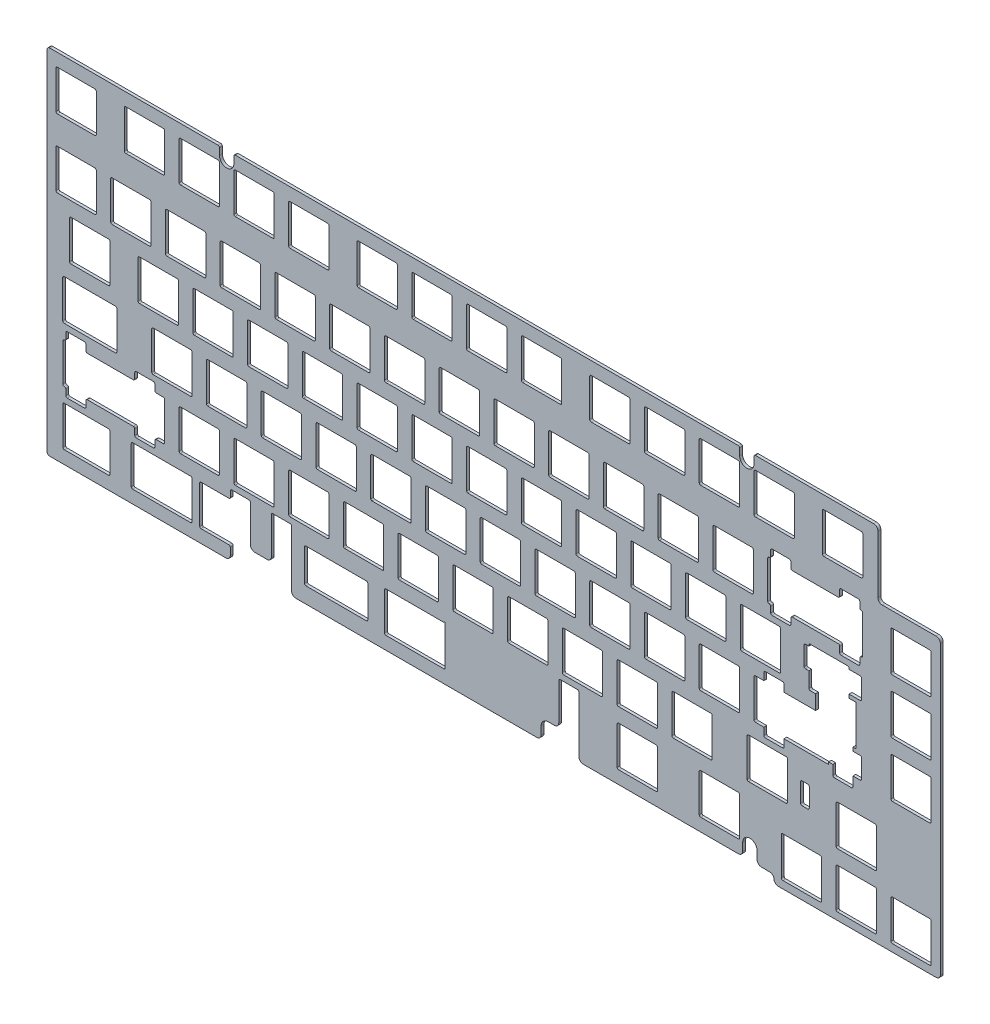
SolidWorks part; units mm, degrees
material "POM Acetal Copolymer"
ref_plane "Front Plane" through (0, 0, 0) normal (0, 0, 1) x (1, 0, 0)
ref_plane "Top Plane" through (0, 0, 0) normal (0, 1, 0) x (1, 0, 0)
ref_plane "Right Plane" through (0, 0, 0) normal (1, 0, 0) x (0, 0, -1)
sketch "Model" plane through (0, 0, 0) normal (0, 0, 1) x (1, 0, 0)
  line L0 (274.4928, 83.607) -> (287.4928, 83.607)
  line L1 (273.9928, 70.107) -> (273.9928, 75.3421)
  line L2 (8.8553, 129.8695) -> (8.8553, 63.082)
  line L3 (67.4518, 130.9695) -> (9.9553, 130.9695)
  line L4 (319.7678, 63.082) -> (319.7678, 106.4532)
  line L5 (195.4959, 7.957) -> (249.4928, 7.957)
  line L6 (86.9959, 28.958) -> (86.9959, 16.157)
  line L7 (187.4959, 29.458) -> (193.4959, 29.458)
  line L8 (193.9959, 28.958) -> (193.9959, 9.457)
  line L9 (186.9959, 16.157) -> (186.9959, 28.958)
  line L10 (87.4959, 29.458) -> (93.4959, 29.458)
  line L11 (126.357, 12.957) -> (126.357, 25.957)
  line L12 (62.0594, 12.957) -> (62.0594, 25.957)
  line L13 (38.2454, 12.957) -> (38.2454, 25.957)
  line L14 (14.4343, 12.957) -> (14.4343, 25.957)
  line L15 (72.207, 12.457) -> (62.5594, 12.457)
  line L16 (62.5594, 26.457) -> (72.207, 26.457)
  line L17 (59.3945, 25.957) -> (59.3945, 12.957)
  line L18 (58.8945, 12.457) -> (38.7454, 12.457)
  line L19 (38.7454, 26.457) -> (58.8945, 26.457)
  line L20 (30.8195, 25.957) -> (30.8195, 12.957)
  line L21 (30.3195, 12.457) -> (14.9343, 12.457)
  line L22 (14.9343, 26.457) -> (30.3195, 26.457)
  line L23 (93.9959, 28.958) -> (93.9959, 9.457)
  line L24 (146.9959, 12.457) -> (126.857, 12.457)
  line L25 (126.857, 26.457) -> (146.9959, 26.457)
  line L26 (147.4959, 26.7823) -> (147.4959, 12.957)
  line L27 (9.9553, 7.957) -> (71.207, 7.957)
  line L28 (95.4959, 7.957) -> (179.3625, 7.957)
  line L29 (263.3678, 5.0945) -> (318.2678, 5.0945)
  line L30 (180.8625, 12.157) -> (180.8625, 9.457)
  line L31 (250.9928, 12.157) -> (250.9928, 9.457)
  line L32 (255.9928, 12.157) -> (255.9928, 9.457)
  line L33 (183.3625, 14.657) -> (185.4959, 14.657)
  line L34 (81.207, 14.657) -> (85.4959, 14.657)
  line L35 (257.4928, 7.957) -> (260.371, 7.957)
  line L36 (8.8553, 63.082) -> (8.8553, 9.057)
  line L37 (319.7678, 63.082) -> (319.7678, 6.5945)
  line L38 (75.4518, 130.9695) -> (248.4268, 130.9695)
  line L39 (256.4268, 130.9695) -> (296.5553, 130.9695)
  line L40 (298.0553, 129.4695) -> (298.0553, 109.4532)
  line L41 (299.5553, 107.9532) -> (318.2678, 107.9532)
  line L42 (271.6572, 41.007) -> (273.6572, 41.007)
  line L43 (274.1572, 40.507) -> (274.1572, 36.507)
  line L44 (273.6572, 36.007) -> (271.6572, 36.007)
  line L45 (271.1572, 36.507) -> (271.1572, 40.507)
  line L46 (260.7295, 105.157) -> (260.7295, 103.157)
  line L47 (268.2295, 102.657) -> (284.2295, 102.657)
  line L48 (268.2295, 88.657) -> (284.2295, 88.657)
  line L49 (261.2295, 105.657) -> (267.2295, 105.657)
  line L50 (261.2295, 85.657) -> (267.2295, 85.657)
  line L51 (267.7295, 103.157) -> (267.7295, 105.157)
  line L52 (267.7295, 88.157) -> (267.7295, 86.157)
  line L53 (291.7295, 105.157) -> (291.7295, 103.157)
  line L54 (291.2295, 105.657) -> (285.2295, 105.657)
  line L55 (291.2295, 85.657) -> (285.2295, 85.657)
  line L56 (284.7295, 103.157) -> (284.7295, 105.157)
  line L57 (284.7295, 88.157) -> (284.7295, 86.157)
  line L58 (258.3508, 50.557) -> (258.3508, 48.057)
  line L59 (265.3508, 50.557) -> (280.8516, 50.557)
  line L60 (258.8508, 67.557) -> (264.8508, 67.557)
  line L61 (258.8508, 47.557) -> (264.8508, 47.557)
  line L62 (265.3508, 64.557) -> (265.3508, 67.057)
  line L63 (265.3508, 50.557) -> (265.3508, 48.057)
  line L64 (288.8508, 47.557) -> (282.8508, 47.557)
  line L65 (282.3508, 51.3421) -> (282.3508, 48.057)
  line L66 (15.4632, 48.0073) -> (15.4632, 46.007)
  line L67 (22.9632, 45.5073) -> (38.9632, 45.5073)
  line L68 (22.9632, 31.5073) -> (38.9632, 31.5073)
  line L69 (15.9632, 48.5073) -> (21.9632, 48.5073)
  line L70 (15.9632, 28.5073) -> (21.9632, 28.5073)
  line L71 (22.4632, 46.0073) -> (22.4632, 48.0073)
  line L72 (22.4632, 31.0073) -> (22.4632, 29.0073)
  line L73 (46.4632, 48.0073) -> (46.4632, 46.007)
  line L74 (45.9632, 48.5073) -> (39.9632, 48.5073)
  line L75 (45.9632, 28.5073) -> (39.9632, 28.5073)
  line L76 (39.4632, 46.0073) -> (39.4632, 48.0073)
  line L77 (39.4632, 31.0073) -> (39.4632, 29.0073)
  line L78 (258.3508, 50.557) -> (255.4453, 50.557)
  line L79 (276.3765, 69.607) -> (274.4928, 69.607)
  line L80 (276.3765, 64.557) -> (276.3765, 69.607)
  line L81 (292.3508, 82.2801) -> (292.3508, 75.8421)
  line L82 (292.3508, 58.2801) -> (292.3508, 51.8421)
  line L83 (291.8508, 82.7801) -> (287.9953, 82.7801)
  line L84 (255.4453, 64.557) -> (258.3508, 64.557)
  line L85 (290.3765, 74.0611) -> (290.3765, 60.0611)
  line L86 (254.9453, 64.057) -> (254.9453, 51.057)
  line L87 (287.9953, 75.3421) -> (291.8508, 75.3421)
  line L88 (289.3508, 58.7801) -> (291.8508, 58.7801)
  line L89 (290.3765, 74.0611) -> (287.9953, 74.0611)
  line L90 (287.9953, 74.0611) -> (287.9953, 75.3421)
  line L91 (289.3508, 58.7801) -> (289.3508, 60.0611)
  line L92 (289.3508, 60.0611) -> (290.3765, 60.0611)
  line L93 (282.3508, 51.3421) -> (280.8516, 51.3421)
  line L94 (280.8516, 51.3421) -> (280.8516, 50.557)
  line L95 (258.3508, 67.057) -> (258.3508, 64.557)
  line L96 (289.3508, 48.057) -> (289.3508, 51.3421)
  line L97 (291.8508, 51.3421) -> (289.3508, 51.3421)
  line L98 (287.9928, 83.107) -> (287.9953, 82.7801)
  line L99 (265.3508, 64.557) -> (276.3765, 64.557)
  line L100 (272.3508, 82.2801) -> (272.3508, 75.8421)
  line L101 (272.8508, 82.7801) -> (273.9928, 82.7801)
  line L102 (273.9928, 75.3421) -> (272.8508, 75.3421)
  line L103 (273.9928, 82.7801) -> (273.9928, 83.107)
  line L104 (259.7053, 89.157) -> (259.7053, 102.157)
  line L105 (292.7553, 102.157) -> (292.7553, 89.157)
  line L106 (291.7295, 86.157) -> (291.7295, 88.157)
  line L107 (292.2295, 88.657) -> (292.2553, 88.657)
  line L108 (292.2295, 102.657) -> (292.2553, 102.657)
  line L109 (260.2053, 102.657) -> (260.2295, 102.657)
  line L110 (260.7295, 86.157) -> (260.7295, 88.157)
  line L111 (260.2295, 88.657) -> (260.2053, 88.657)
  line L112 (49.8678, 45.007) -> (49.8678, 32.007)
  line L113 (46.4632, 29.0073) -> (46.4632, 31.007)
  line L114 (46.9632, 31.507) -> (49.3678, 31.507)
  line L115 (46.9632, 45.507) -> (49.3678, 45.507)
  line L116 (14.4365, 32.007) -> (14.4365, 45.007)
  line L117 (15.4632, 29.0073) -> (15.4632, 31.007)
  line L118 (14.9632, 31.507) -> (14.9365, 31.507)
  line L119 (14.9365, 45.507) -> (14.9632, 45.507)
  line L120 (79.707, 28.958) -> (79.707, 16.157)
  line L121 (72.707, 11.957) -> (72.707, 9.457)
  line L122 (72.707, 26.957) -> (72.707, 28.958)
  line L123 (73.207, 29.458) -> (79.207, 29.458)
  line L124 (120.5413, 13.957) -> (120.5413, 24.957)
  line L125 (99.0413, 13.457) -> (120.0413, 13.457)
  line L126 (98.5413, 24.957) -> (98.5413, 13.957)
  line L127 (120.0413, 25.457) -> (99.0413, 25.457)
  line L144 (12.5303, 112.4445) -> (25.5803, 112.4445)
  line L145 (26.0803, 112.9445) -> (26.0803, 125.9945)
  line L146 (25.5803, 126.4945) -> (12.5303, 126.4945)
  line L147 (12.0303, 125.9945) -> (12.0303, 112.9445)
  line L148 (36.3428, 112.4445) -> (49.3928, 112.4445)
  line L149 (49.8928, 112.9445) -> (49.8928, 125.9945)
  line L150 (49.3928, 126.4945) -> (36.3428, 126.4945)
  line L151 (35.8428, 125.9945) -> (35.8428, 112.9445)
  line L152 (93.4928, 112.4445) -> (106.5428, 112.4445)
  line L153 (107.0428, 112.9445) -> (107.0428, 125.9945)
  line L154 (106.5428, 126.4945) -> (93.4928, 126.4945)
  line L155 (92.9928, 125.9945) -> (92.9928, 112.9445)
  line L156 (117.3053, 112.4445) -> (130.3553, 112.4445)
  line L157 (130.8553, 112.9445) -> (130.8553, 125.9945)
  line L158 (130.3553, 126.4945) -> (117.3053, 126.4945)
  line L159 (116.8053, 125.9945) -> (116.8053, 112.9445)
  line L160 (136.3553, 112.4445) -> (149.4053, 112.4445)
  line L161 (149.9053, 112.9445) -> (149.9053, 125.9945)
  line L162 (149.4053, 126.4945) -> (136.3553, 126.4945)
  line L163 (135.8553, 125.9945) -> (135.8553, 112.9445)
  line L164 (155.4053, 112.4445) -> (168.4553, 112.4445)
  line L165 (168.9553, 112.9445) -> (168.9553, 125.9945)
  line L166 (168.4553, 126.4945) -> (155.4053, 126.4945)
  line L167 (154.9053, 125.9945) -> (154.9053, 112.9445)
  line L168 (174.4553, 112.4445) -> (187.5053, 112.4445)
  line L169 (188.0053, 112.9445) -> (188.0053, 125.9945)
  line L170 (187.5053, 126.4945) -> (174.4553, 126.4945)
  line L171 (173.9553, 125.9945) -> (173.9553, 112.9445)
  line L172 (198.2678, 112.4445) -> (211.3178, 112.4445)
  line L173 (211.8178, 112.9445) -> (211.8178, 125.9945)
  line L174 (211.3178, 126.4945) -> (198.2678, 126.4945)
  line L175 (197.7678, 125.9945) -> (197.7678, 112.9445)
  line L176 (217.3178, 112.4445) -> (230.3678, 112.4445)
  line L177 (230.8678, 112.9445) -> (230.8678, 125.9945)
  line L178 (230.3678, 126.4945) -> (217.3178, 126.4945)
  line L179 (216.8178, 125.9945) -> (216.8178, 112.9445)
  line L180 (279.2303, 112.4445) -> (292.2803, 112.4445)
  line L181 (292.7803, 112.9445) -> (292.7803, 125.9945)
  line L182 (292.2803, 126.4945) -> (279.2303, 126.4945)
  line L183 (278.7303, 125.9945) -> (278.7303, 112.9445)
  line L184 (303.0428, 88.632) -> (316.0928, 88.632)
  line L185 (316.5928, 89.132) -> (316.5928, 102.182)
  line L186 (316.0928, 102.682) -> (303.0428, 102.682)
  line L187 (302.5428, 102.182) -> (302.5428, 89.132)
  line L188 (283.9928, 26.7195) -> (297.0428, 26.7195)
  line L189 (297.5428, 27.2195) -> (297.5428, 40.2695)
  line L190 (297.0428, 40.7695) -> (283.9928, 40.7695)
  line L191 (283.4928, 40.2695) -> (283.4928, 27.2195)
  line L192 (303.0428, 7.6695) -> (316.0928, 7.6695)
  line L193 (316.5928, 8.1695) -> (316.5928, 21.2195)
  line L194 (316.0928, 21.7195) -> (303.0428, 21.7195)
  line L195 (302.5428, 21.2195) -> (302.5428, 8.1695)
  line L196 (283.9928, 7.6695) -> (297.0428, 7.6695)
  line L197 (297.5428, 8.1695) -> (297.5428, 21.2195)
  line L198 (297.0428, 21.7195) -> (283.9928, 21.7195)
  line L199 (283.4928, 21.2195) -> (283.4928, 8.1695)
  line L200 (264.9428, 7.6695) -> (277.9928, 7.6695)
  line L201 (278.4928, 8.1695) -> (278.4928, 21.2195)
  line L202 (277.9928, 21.7195) -> (264.9428, 21.7195)
  line L203 (264.4428, 21.2195) -> (264.4428, 8.1695)
  line L204 (236.3678, 12.432) -> (249.4178, 12.432)
  line L205 (249.9178, 12.932) -> (249.9178, 25.982)
  line L206 (249.4178, 26.482) -> (236.3678, 26.482)
  line L207 (235.8678, 25.982) -> (235.8678, 12.932)
  line L208 (207.7928, 12.432) -> (220.8428, 12.432)
  line L209 (221.3428, 12.932) -> (221.3428, 25.982)
  line L210 (220.8428, 26.482) -> (207.7928, 26.482)
  line L211 (207.2928, 25.982) -> (207.2928, 12.932)
  line L212 (253.0365, 31.482) -> (266.0865, 31.482)
  line L213 (266.5865, 31.982) -> (266.5865, 45.032)
  line L214 (266.0865, 45.532) -> (253.0365, 45.532)
  line L215 (252.5365, 45.032) -> (252.5365, 31.982)
  line L216 (226.8428, 31.482) -> (239.8928, 31.482)
  line L217 (240.3928, 31.982) -> (240.3928, 45.032)
  line L218 (239.8928, 45.532) -> (226.8428, 45.532)
  line L219 (226.3428, 45.032) -> (226.3428, 31.982)
  line L220 (207.7928, 31.482) -> (220.8428, 31.482)
  line L221 (221.3428, 31.982) -> (221.3428, 45.032)
  line L222 (220.8428, 45.532) -> (207.7928, 45.532)
  line L223 (207.2928, 45.032) -> (207.2928, 31.982)
  line L224 (188.7428, 31.482) -> (201.7928, 31.482)
  line L225 (202.2928, 31.982) -> (202.2928, 45.032)
  line L226 (201.7928, 45.532) -> (188.7428, 45.532)
  line L227 (188.2428, 45.032) -> (188.2428, 31.982)
  line L228 (169.6928, 31.482) -> (182.7428, 31.482)
  line L229 (183.2428, 31.982) -> (183.2428, 45.032)
  line L230 (182.7428, 45.532) -> (169.6928, 45.532)
  line L231 (169.1928, 45.032) -> (169.1928, 31.982)
  line L232 (150.6428, 31.482) -> (163.6928, 31.482)
  line L233 (164.1928, 31.982) -> (164.1928, 45.032)
  line L234 (163.6928, 45.532) -> (150.6428, 45.532)
  line L235 (150.1428, 45.032) -> (150.1428, 31.982)
  line L236 (131.5928, 31.482) -> (144.6428, 31.482)
  line L237 (145.1428, 31.982) -> (145.1428, 45.032)
  line L238 (144.6428, 45.532) -> (131.5928, 45.532)
  line L239 (131.0928, 45.032) -> (131.0928, 31.982)
  line L240 (112.5428, 31.482) -> (125.5928, 31.482)
  line L241 (126.0928, 31.982) -> (126.0928, 45.032)
  line L242 (125.5928, 45.532) -> (112.5428, 45.532)
  line L243 (112.0428, 45.032) -> (112.0428, 31.982)
  line L244 (93.4928, 31.482) -> (106.5428, 31.482)
  line L245 (107.0428, 31.982) -> (107.0428, 45.032)
  line L246 (106.5428, 45.532) -> (93.4928, 45.532)
  line L247 (92.9928, 45.032) -> (92.9928, 31.982)
  line L248 (74.4428, 31.482) -> (87.4928, 31.482)
  line L249 (87.9928, 31.982) -> (87.9928, 45.032)
  line L250 (87.4928, 45.532) -> (74.4428, 45.532)
  line L251 (73.9428, 45.032) -> (73.9428, 31.982)
  line L252 (55.3928, 31.482) -> (68.4428, 31.482)
  line L253 (68.9428, 31.982) -> (68.9428, 45.032)
  line L254 (68.4428, 45.532) -> (55.3928, 45.532)
  line L255 (54.8928, 45.032) -> (54.8928, 31.982)
  line L256 (45.8678, 50.532) -> (58.9178, 50.532)
  line L257 (59.4178, 51.032) -> (59.4178, 64.082)
  line L258 (58.9178, 64.582) -> (45.8678, 64.582)
  line L259 (45.3678, 64.082) -> (45.3678, 51.032)
  line L260 (64.9178, 50.532) -> (77.9678, 50.532)
  line L261 (78.4678, 51.032) -> (78.4678, 64.082)
  line L262 (77.9678, 64.582) -> (64.9178, 64.582)
  line L263 (64.4178, 64.082) -> (64.4178, 51.032)
  line L264 (83.9678, 50.532) -> (97.0178, 50.532)
  line L265 (97.5178, 51.032) -> (97.5178, 64.082)
  line L266 (97.0178, 64.582) -> (83.9678, 64.582)
  line L267 (83.4678, 64.082) -> (83.4678, 51.032)
  line L268 (103.0178, 50.532) -> (116.0678, 50.532)
  line L269 (116.5678, 51.032) -> (116.5678, 64.082)
  line L270 (116.0678, 64.582) -> (103.0178, 64.582)
  line L271 (102.5178, 64.082) -> (102.5178, 51.032)
  line L272 (122.0678, 50.532) -> (135.1178, 50.532)
  line L273 (135.6178, 51.032) -> (135.6178, 64.082)
  line L274 (135.1178, 64.582) -> (122.0678, 64.582)
  line L275 (121.5678, 64.082) -> (121.5678, 51.032)
  line L276 (141.1178, 50.532) -> (154.1678, 50.532)
  line L277 (154.6678, 51.032) -> (154.6678, 64.082)
  line L278 (154.1678, 64.582) -> (141.1178, 64.582)
  line L279 (140.6178, 64.082) -> (140.6178, 51.032)
  line L280 (160.1678, 50.532) -> (173.2178, 50.532)
  line L281 (173.7178, 51.032) -> (173.7178, 64.082)
  line L282 (173.2178, 64.582) -> (160.1678, 64.582)
  line L283 (159.6678, 64.082) -> (159.6678, 51.032)
  line L284 (179.2178, 50.532) -> (192.2678, 50.532)
  line L285 (192.7678, 51.032) -> (192.7678, 64.082)
  line L286 (192.2678, 64.582) -> (179.2178, 64.582)
  line L287 (178.7178, 64.082) -> (178.7178, 51.032)
  line L288 (198.2678, 50.532) -> (211.3178, 50.532)
  line L289 (211.8178, 51.032) -> (211.8178, 64.082)
  line L290 (211.3178, 64.582) -> (198.2678, 64.582)
  line L291 (197.7678, 64.082) -> (197.7678, 51.032)
  line L292 (217.3178, 50.532) -> (230.3678, 50.532)
  line L293 (230.8678, 51.032) -> (230.8678, 64.082)
  line L294 (230.3678, 64.582) -> (217.3178, 64.582)
  line L295 (216.8178, 64.082) -> (216.8178, 51.032)
  line L296 (236.3678, 50.532) -> (249.4178, 50.532)
  line L297 (249.9178, 51.032) -> (249.9178, 64.082)
  line L298 (249.4178, 64.582) -> (236.3678, 64.582)
  line L299 (235.8678, 64.082) -> (235.8678, 51.032)
  line L300 (17.2928, 69.582) -> (30.3428, 69.582)
  line L301 (30.8428, 70.082) -> (30.8428, 83.132)
  line L302 (30.3428, 83.632) -> (17.2928, 83.632)
  line L303 (16.7928, 83.132) -> (16.7928, 70.082)
  line L304 (12.5303, 88.632) -> (25.5803, 88.632)
  line L305 (26.0803, 89.132) -> (26.0803, 102.182)
  line L306 (25.5803, 102.682) -> (12.5303, 102.682)
  line L307 (12.0303, 102.182) -> (12.0303, 89.132)
  line L308 (31.5803, 88.632) -> (44.6303, 88.632)
  line L309 (45.1303, 89.132) -> (45.1303, 102.182)
  line L310 (44.6303, 102.682) -> (31.5803, 102.682)
  line L311 (31.0803, 102.182) -> (31.0803, 89.132)
  line L312 (50.6303, 88.632) -> (63.6803, 88.632)
  line L313 (64.1803, 89.132) -> (64.1803, 102.182)
  line L314 (63.6803, 102.682) -> (50.6303, 102.682)
  line L315 (50.1303, 102.182) -> (50.1303, 89.132)
  line L316 (69.6803, 88.632) -> (82.7303, 88.632)
  line L317 (83.2303, 89.132) -> (83.2303, 102.182)
  line L318 (82.7303, 102.682) -> (69.6803, 102.682)
  line L319 (69.1803, 102.182) -> (69.1803, 89.132)
  line L320 (88.7303, 88.632) -> (101.7803, 88.632)
  line L321 (102.2803, 89.132) -> (102.2803, 102.182)
  line L322 (101.7803, 102.682) -> (88.7303, 102.682)
  line L323 (88.2303, 102.182) -> (88.2303, 89.132)
  line L324 (107.7803, 88.632) -> (120.8303, 88.632)
  line L325 (121.3303, 89.132) -> (121.3303, 102.182)
  line L326 (120.8303, 102.682) -> (107.7803, 102.682)
  line L327 (107.2803, 102.182) -> (107.2803, 89.132)
  line L328 (126.8303, 88.632) -> (139.8803, 88.632)
  line L329 (140.3803, 89.132) -> (140.3803, 102.182)
  line L330 (139.8803, 102.682) -> (126.8303, 102.682)
  line L331 (126.3303, 102.182) -> (126.3303, 89.132)
  line L332 (145.8803, 88.632) -> (158.9303, 88.632)
  line L333 (159.4303, 89.132) -> (159.4303, 102.182)
  line L334 (158.9303, 102.682) -> (145.8803, 102.682)
  line L335 (145.3803, 102.182) -> (145.3803, 89.132)
  line L336 (164.9303, 88.632) -> (177.9803, 88.632)
  line L337 (178.4803, 89.132) -> (178.4803, 102.182)
  line L338 (177.9803, 102.682) -> (164.9303, 102.682)
  line L339 (164.4303, 102.182) -> (164.4303, 89.132)
  line L340 (183.9803, 88.632) -> (197.0303, 88.632)
  line L341 (197.5303, 89.132) -> (197.5303, 102.182)
  line L342 (197.0303, 102.682) -> (183.9803, 102.682)
  line L343 (183.4803, 102.182) -> (183.4803, 89.132)
  line L344 (203.0303, 88.632) -> (216.0803, 88.632)
  line L345 (216.5803, 89.132) -> (216.5803, 102.182)
  line L346 (216.0803, 102.682) -> (203.0303, 102.682)
  line L347 (202.5303, 102.182) -> (202.5303, 89.132)
  line L348 (222.0803, 88.632) -> (235.1303, 88.632)
  line L349 (235.6303, 89.132) -> (235.6303, 102.182)
  line L350 (235.1303, 102.682) -> (222.0803, 102.682)
  line L351 (221.5803, 102.182) -> (221.5803, 89.132)
  line L352 (241.1303, 88.632) -> (254.1803, 88.632)
  line L353 (254.6803, 89.132) -> (254.6803, 102.182)
  line L354 (254.1803, 102.682) -> (241.1303, 102.682)
  line L355 (240.6303, 102.182) -> (240.6303, 89.132)
  line L356 (41.1053, 69.582) -> (54.1553, 69.582)
  line L357 (54.6553, 70.082) -> (54.6553, 83.132)
  line L358 (54.1553, 83.632) -> (41.1053, 83.632)
  line L359 (40.6053, 83.132) -> (40.6053, 70.082)
  line L360 (60.1553, 69.582) -> (73.2053, 69.582)
  line L361 (73.7053, 70.082) -> (73.7053, 83.132)
  line L362 (73.2053, 83.632) -> (60.1553, 83.632)
  line L363 (59.6553, 83.132) -> (59.6553, 70.082)
  line L364 (79.2053, 69.582) -> (92.2553, 69.582)
  line L365 (92.7553, 70.082) -> (92.7553, 83.132)
  line L366 (92.2553, 83.632) -> (79.2053, 83.632)
  line L367 (78.7053, 83.132) -> (78.7053, 70.082)
  line L368 (98.2553, 69.582) -> (111.3053, 69.582)
  line L369 (111.8053, 70.082) -> (111.8053, 83.132)
  line L370 (111.3053, 83.632) -> (98.2553, 83.632)
  line L371 (97.7553, 83.132) -> (97.7553, 70.082)
  line L372 (117.3053, 69.582) -> (130.3553, 69.582)
  line L373 (130.8553, 70.082) -> (130.8553, 83.132)
  line L374 (130.3553, 83.632) -> (117.3053, 83.632)
  line L375 (116.8053, 83.132) -> (116.8053, 70.082)
  line L376 (136.3553, 69.582) -> (149.4053, 69.582)
  line L377 (149.9053, 70.082) -> (149.9053, 83.132)
  line L378 (149.4053, 83.632) -> (136.3553, 83.632)
  line L379 (135.8553, 83.132) -> (135.8553, 70.082)
  line L380 (155.4053, 69.582) -> (168.4553, 69.582)
  line L381 (168.9553, 70.082) -> (168.9553, 83.132)
  line L382 (168.4553, 83.632) -> (155.4053, 83.632)
  line L383 (154.9053, 83.132) -> (154.9053, 70.082)
  line L384 (174.4553, 69.582) -> (187.5053, 69.582)
  line L385 (188.0053, 70.082) -> (188.0053, 83.132)
  line L386 (187.5053, 83.632) -> (174.4553, 83.632)
  line L387 (173.9553, 83.132) -> (173.9553, 70.082)
  line L388 (193.5053, 69.582) -> (206.5553, 69.582)
  line L389 (207.0553, 70.082) -> (207.0553, 83.132)
  line L390 (206.5553, 83.632) -> (193.5053, 83.632)
  line L391 (193.0053, 83.132) -> (193.0053, 70.082)
  line L392 (212.5553, 69.582) -> (225.6053, 69.582)
  line L393 (226.1053, 70.082) -> (226.1053, 83.132)
  line L394 (225.6053, 83.632) -> (212.5553, 83.632)
  line L395 (212.0553, 83.132) -> (212.0553, 70.082)
  line L396 (231.6053, 69.582) -> (244.6553, 69.582)
  line L397 (245.1553, 70.082) -> (245.1553, 83.132)
  line L398 (244.6553, 83.632) -> (231.6053, 83.632)
  line L399 (231.1053, 83.132) -> (231.1053, 70.082)
  line L400 (250.6553, 69.582) -> (263.7053, 69.582)
  line L401 (264.2053, 70.082) -> (264.2053, 83.132)
  line L402 (263.7053, 83.632) -> (250.6553, 83.632)
  line L403 (250.1553, 83.132) -> (250.1553, 70.082)
  line L404 (303.0428, 69.582) -> (316.0928, 69.582)
  line L405 (316.5928, 70.082) -> (316.5928, 83.132)
  line L406 (316.0928, 83.632) -> (303.0428, 83.632)
  line L407 (302.5428, 83.132) -> (302.5428, 70.082)
  line L408 (303.0678, 64.582) -> (316.1178, 64.582)
  line L409 (302.5428, 51.057) -> (302.5428, 64.057)
  line L410 (316.0678, 50.532) -> (303.0678, 50.532)
  line L411 (316.5928, 64.107) -> (316.5928, 51.057)
  line L412 (32.699, 50.507) -> (14.9365, 50.507)
  line L413 (33.249, 64.057) -> (33.249, 51.057)
  line L414 (14.9365, 64.607) -> (32.699, 64.607)
  line L415 (14.3865, 51.057) -> (14.3865, 64.057)
  line L416 (236.3678, 112.4445) -> (249.4178, 112.4445)
  line L417 (249.9178, 112.9445) -> (249.9178, 125.9945)
  line L418 (249.4178, 126.4945) -> (236.3678, 126.4945)
  line L419 (235.8678, 125.9945) -> (235.8678, 112.9445)
  line L420 (255.4178, 112.4445) -> (268.4678, 112.4445)
  line L421 (268.9678, 112.9445) -> (268.9678, 125.9945)
  line L422 (268.4678, 126.4945) -> (255.4178, 126.4945)
  line L423 (254.9178, 125.9945) -> (254.9178, 112.9445)
  line L424 (55.3928, 112.4445) -> (68.4428, 112.4445)
  line L425 (68.9428, 112.9445) -> (68.9428, 125.9945)
  line L426 (68.4428, 126.4945) -> (55.3928, 126.4945)
  line L427 (54.8928, 125.9945) -> (54.8928, 112.9445)
  line L428 (74.4428, 112.4445) -> (87.4928, 112.4445)
  line L429 (87.9928, 112.9445) -> (87.9928, 125.9945)
  line L430 (87.4928, 126.4945) -> (74.4428, 126.4945)
  line L431 (73.9428, 125.9945) -> (73.9428, 112.9445)
  line L432 (67.4518, 130.9695) -> (75.4518, 130.9695)
  line L433 (248.4268, 130.9695) -> (256.4268, 130.9695)
  arc A0 (319.7678, 106.4532) -> (318.2678, 107.9532) centre (318.2678, 106.4532) ccw
  arc A1 (318.2678, 5.0945) -> (319.7678, 6.5945) centre (318.2678, 6.5945) ccw
  arc A2 (193.9959, 9.457) -> (195.4959, 7.957) centre (195.4959, 9.457) ccw
  arc A3 (273.9928, 70.107) -> (274.4928, 69.607) centre (274.4928, 70.107) ccw
  arc A4 (287.9928, 83.107) -> (287.4928, 83.607) centre (287.4928, 83.107) ccw
  arc A5 (274.4928, 83.607) -> (273.9928, 83.107) centre (274.4928, 83.107) ccw
  arc A6 (8.8553, 9.057) -> (9.9553, 7.957) centre (9.9553, 9.057) ccw
  arc A7 (9.9553, 130.9695) -> (8.8553, 129.8695) centre (9.9553, 129.8695) ccw
  arc A8 (85.4959, 14.657) -> (86.9959, 16.157) centre (85.4959, 16.157) ccw
  arc A9 (193.9959, 28.958) -> (193.4959, 29.458) centre (193.4959, 28.958) ccw
  arc A10 (187.4959, 29.458) -> (186.9959, 28.958) centre (187.4959, 28.958) ccw
  arc A11 (185.4959, 14.657) -> (186.9959, 16.157) centre (185.4959, 16.157) ccw
  arc A12 (87.4959, 29.458) -> (86.9959, 28.958) centre (87.4959, 28.958) ccw
  arc A13 (126.357, 12.957) -> (126.857, 12.457) centre (126.857, 12.957) ccw
  arc A14 (93.9959, 28.958) -> (93.4959, 29.458) centre (93.4959, 28.958) ccw
  arc A15 (38.7454, 26.457) -> (38.2454, 25.957) centre (38.7454, 25.957) ccw
  arc A16 (14.9343, 26.457) -> (14.4343, 25.957) centre (14.9343, 25.957) ccw
  arc A17 (62.0594, 12.957) -> (62.5594, 12.457) centre (62.5594, 12.957) ccw
  arc A18 (62.5594, 26.457) -> (62.0594, 25.957) centre (62.5594, 25.957) ccw
  arc A19 (38.2454, 12.957) -> (38.7454, 12.457) centre (38.7454, 12.957) ccw
  arc A20 (58.8945, 12.457) -> (59.3945, 12.957) centre (58.8945, 12.957) ccw
  arc A21 (59.3945, 25.957) -> (58.8945, 26.457) centre (58.8945, 25.957) ccw
  arc A22 (30.3195, 12.457) -> (30.8195, 12.957) centre (30.3195, 12.957) ccw
  arc A23 (14.4343, 12.957) -> (14.9343, 12.457) centre (14.9343, 12.957) ccw
  arc A24 (30.8195, 25.957) -> (30.3195, 26.457) centre (30.3195, 25.957) ccw
  arc A25 (126.857, 26.457) -> (126.357, 25.957) centre (126.857, 25.957) ccw
  arc A26 (146.9959, 12.457) -> (147.4959, 12.957) centre (146.9959, 12.957) ccw
  arc A27 (147.4959, 26.7823) -> (146.9959, 26.457) centre (147.4647, 26.2833) ccw
  arc A28 (93.9959, 9.457) -> (95.4959, 7.957) centre (95.4959, 9.457) ccw
  arc A29 (261.8694, 6.5258) -> (263.3678, 5.0945) centre (263.3678, 6.5945) ccw
  arc A30 (261.8694, 6.5258) -> (260.371, 7.957) centre (260.371, 6.457) ccw
  arc A31 (179.3625, 7.957) -> (180.8625, 9.457) centre (179.3625, 9.457) ccw
  arc A32 (255.9928, 9.457) -> (257.4928, 7.957) centre (257.4928, 9.457) ccw
  arc A33 (249.4928, 7.957) -> (250.9928, 9.457) centre (249.4928, 9.457) ccw
  arc A34 (255.9928, 12.157) -> (250.9928, 12.157) centre (253.4928, 12.157) ccw
  arc A35 (183.3625, 14.657) -> (180.8625, 12.157) centre (183.3625, 12.157) ccw
  arc A36 (298.0553, 129.4695) -> (296.5553, 130.9695) centre (296.5553, 129.4695) ccw
  arc A37 (298.0553, 109.4532) -> (299.5553, 107.9532) centre (299.5553, 109.4532) ccw
  arc A38 (271.6572, 41.007) -> (271.1572, 40.507) centre (271.6572, 40.507) ccw
  arc A39 (274.1572, 40.507) -> (273.6572, 41.007) centre (273.6572, 40.507) ccw
  arc A40 (273.6572, 36.007) -> (274.1572, 36.507) centre (273.6572, 36.507) ccw
  arc A41 (271.1572, 36.507) -> (271.6572, 36.007) centre (271.6572, 36.507) ccw
  arc A42 (260.2295, 102.657) -> (260.7295, 103.157) centre (260.2295, 103.157) ccw
  arc A43 (267.7295, 103.157) -> (268.2295, 102.657) centre (268.2295, 103.157) ccw
  arc A44 (261.2295, 105.657) -> (260.7295, 105.157) centre (261.2295, 105.157) ccw
  arc A45 (260.7295, 86.157) -> (261.2295, 85.657) centre (261.2295, 86.157) ccw
  arc A46 (267.7295, 105.157) -> (267.2295, 105.657) centre (267.2295, 105.157) ccw
  arc A47 (268.2295, 88.657) -> (267.7295, 88.157) centre (268.2295, 88.157) ccw
  arc A48 (267.2295, 85.657) -> (267.7295, 86.157) centre (267.2295, 86.157) ccw
  arc A49 (284.2295, 102.657) -> (284.7295, 103.157) centre (284.2295, 103.157) ccw
  arc A50 (291.7295, 105.157) -> (291.2295, 105.657) centre (291.2295, 105.157) ccw
  arc A51 (291.2295, 85.657) -> (291.7295, 86.157) centre (291.2295, 86.157) ccw
  arc A52 (285.2295, 105.657) -> (284.7295, 105.157) centre (285.2295, 105.157) ccw
  arc A53 (284.7295, 88.157) -> (284.2295, 88.657) centre (284.2295, 88.157) ccw
  arc A54 (284.7295, 86.157) -> (285.2295, 85.657) centre (285.2295, 86.157) ccw
  arc A55 (258.8508, 67.557) -> (258.3508, 67.057) centre (258.8508, 67.057) ccw
  arc A56 (258.3508, 48.057) -> (258.8508, 47.557) centre (258.8508, 48.057) ccw
  arc A57 (265.3508, 67.057) -> (264.8508, 67.557) centre (264.8508, 67.057) ccw
  arc A58 (264.8508, 47.557) -> (265.3508, 48.057) centre (264.8508, 48.057) ccw
  arc A59 (288.8508, 47.557) -> (289.3508, 48.057) centre (288.8508, 48.057) ccw
  arc A60 (282.3508, 48.057) -> (282.8508, 47.557) centre (282.8508, 48.057) ccw
  arc A61 (14.9632, 45.507) -> (15.4632, 46.007) centre (14.9632, 46.007) ccw
  arc A62 (22.4632, 46.0073) -> (22.9632, 45.5073) centre (22.9632, 46.0073) ccw
  arc A63 (15.9632, 48.5073) -> (15.4632, 48.0073) centre (15.9632, 48.0073) ccw
  arc A64 (15.4632, 29.0073) -> (15.9632, 28.5073) centre (15.9632, 29.0073) ccw
  arc A65 (22.4632, 48.0073) -> (21.9632, 48.5073) centre (21.9632, 48.0073) ccw
  arc A66 (22.9632, 31.5073) -> (22.4632, 31.0073) centre (22.9632, 31.0073) ccw
  arc A67 (21.9632, 28.5073) -> (22.4632, 29.0073) centre (21.9632, 29.0073) ccw
  arc A68 (38.9632, 45.5073) -> (39.4632, 46.0073) centre (38.9632, 46.0073) ccw
  arc A69 (46.4632, 48.0073) -> (45.9632, 48.5073) centre (45.9632, 48.0073) ccw
  arc A70 (45.9632, 28.5073) -> (46.4632, 29.0073) centre (45.9632, 29.0073) ccw
  arc A71 (39.9632, 48.5073) -> (39.4632, 48.0073) centre (39.9632, 48.0073) ccw
  arc A72 (39.4632, 31.0073) -> (38.9632, 31.5073) centre (38.9632, 31.0073) ccw
  arc A73 (39.4632, 29.0073) -> (39.9632, 28.5073) centre (39.9632, 29.0073) ccw
  arc A74 (291.8508, 51.3421) -> (292.3508, 51.8421) centre (291.8508, 51.8421) ccw
  arc A75 (292.3508, 82.2801) -> (291.8508, 82.7801) centre (291.8508, 82.2801) ccw
  arc A76 (292.3508, 58.2801) -> (291.8508, 58.7801) centre (291.8508, 58.2801) ccw
  arc A77 (291.8508, 75.3421) -> (292.3508, 75.8421) centre (291.8508, 75.8421) ccw
  arc A78 (272.8508, 82.7801) -> (272.3508, 82.2801) centre (272.8508, 82.2801) ccw
  arc A79 (272.3508, 75.8421) -> (272.8508, 75.3421) centre (272.8508, 75.8421) ccw
  arc A80 (259.7053, 89.157) -> (260.2053, 88.657) centre (260.2053, 89.157) ccw
  arc A81 (260.2053, 102.657) -> (259.7053, 102.157) centre (260.2053, 102.157) ccw
  arc A82 (292.2553, 88.657) -> (292.7553, 89.157) centre (292.2553, 89.157) ccw
  arc A83 (292.7553, 102.157) -> (292.2553, 102.657) centre (292.2553, 102.157) ccw
  arc A84 (292.2295, 88.657) -> (291.7295, 88.157) centre (292.2295, 88.157) ccw
  arc A85 (291.7295, 103.157) -> (292.2295, 102.657) centre (292.2295, 103.157) ccw
  arc A86 (260.7295, 88.157) -> (260.2295, 88.657) centre (260.2295, 88.157) ccw
  arc A87 (49.3678, 31.507) -> (49.8678, 32.007) centre (49.3678, 32.007) ccw
  arc A88 (49.8678, 45.007) -> (49.3678, 45.507) centre (49.3678, 45.007) ccw
  arc A89 (46.9632, 31.507) -> (46.4632, 31.007) centre (46.9632, 31.007) ccw
  arc A90 (46.4632, 46.007) -> (46.9632, 45.507) centre (46.9632, 46.007) ccw
  arc A91 (14.4365, 32.007) -> (14.9365, 31.507) centre (14.9365, 32.007) ccw
  arc A92 (14.9365, 45.507) -> (14.4365, 45.007) centre (14.9365, 45.007) ccw
  arc A93 (15.4632, 31.007) -> (14.9632, 31.507) centre (14.9632, 31.007) ccw
  arc A94 (72.707, 11.957) -> (72.207, 12.457) centre (72.207, 11.957) ccw
  arc A95 (72.207, 26.457) -> (72.707, 26.957) centre (72.207, 26.957) ccw
  arc A96 (73.207, 29.458) -> (72.707, 28.958) centre (73.207, 28.958) ccw
  arc A97 (79.707, 28.958) -> (79.207, 29.458) centre (79.207, 28.958) ccw
  arc A98 (71.207, 7.957) -> (72.707, 9.457) centre (71.207, 9.457) ccw
  arc A99 (79.707, 16.157) -> (81.207, 14.657) centre (81.207, 16.157) ccw
  arc A100 (255.4453, 64.557) -> (254.9453, 64.057) centre (255.4453, 64.057) ccw
  arc A101 (254.9453, 51.057) -> (255.4453, 50.557) centre (255.4453, 51.057) ccw
  arc A102 (120.0413, 13.457) -> (120.5413, 13.957) centre (120.0413, 13.957) ccw
  arc A103 (98.5413, 13.957) -> (99.0413, 13.457) centre (99.0413, 13.957) ccw
  arc A104 (99.0413, 25.457) -> (98.5413, 24.957) centre (99.0413, 24.957) ccw
  arc A105 (120.5413, 24.957) -> (120.0413, 25.457) centre (120.0413, 24.957) ccw
  arc A134 (303.0678, 64.582) -> (302.5428, 64.057) centre (303.0678, 64.057) ccw
  arc A135 (302.5428, 51.057) -> (303.0678, 50.532) centre (303.0678, 51.057) ccw
  arc A136 (316.0678, 50.532) -> (316.5928, 51.057) centre (316.0678, 51.057) ccw
  arc A137 (316.5928, 64.107) -> (316.1178, 64.582) centre (316.1178, 64.107) ccw
  arc A138 (14.3865, 51.057) -> (14.9365, 50.507) centre (14.9365, 51.057) ccw
  arc A139 (32.699, 50.507) -> (33.249, 51.057) centre (32.699, 51.057) ccw
  arc A140 (33.249, 64.057) -> (32.699, 64.607) centre (32.699, 64.057) ccw
  arc A141 (14.9365, 64.607) -> (14.3865, 64.057) centre (14.9365, 64.057) ccw
  arc A142 (25.5803, 112.4445) -> (26.0803, 112.9445) centre (25.5803, 112.9445) ccw
  arc A143 (26.0803, 125.9945) -> (25.5803, 126.4945) centre (25.5803, 125.9945) ccw
  arc A144 (12.5303, 126.4945) -> (12.0303, 125.9945) centre (12.5303, 125.9945) ccw
  arc A145 (12.0303, 112.9445) -> (12.5303, 112.4445) centre (12.5303, 112.9445) ccw
  arc A146 (49.3928, 112.4445) -> (49.8928, 112.9445) centre (49.3928, 112.9445) ccw
  arc A147 (49.8928, 125.9945) -> (49.3928, 126.4945) centre (49.3928, 125.9945) ccw
  arc A148 (36.3428, 126.4945) -> (35.8428, 125.9945) centre (36.3428, 125.9945) ccw
  arc A149 (35.8428, 112.9445) -> (36.3428, 112.4445) centre (36.3428, 112.9445) ccw
  arc A150 (106.5428, 112.4445) -> (107.0428, 112.9445) centre (106.5428, 112.9445) ccw
  arc A151 (107.0428, 125.9945) -> (106.5428, 126.4945) centre (106.5428, 125.9945) ccw
  arc A152 (93.4928, 126.4945) -> (92.9928, 125.9945) centre (93.4928, 125.9945) ccw
  arc A153 (92.9928, 112.9445) -> (93.4928, 112.4445) centre (93.4928, 112.9445) ccw
  arc A154 (130.3553, 112.4445) -> (130.8553, 112.9445) centre (130.3553, 112.9445) ccw
  arc A155 (130.8553, 125.9945) -> (130.3553, 126.4945) centre (130.3553, 125.9945) ccw
  arc A156 (117.3053, 126.4945) -> (116.8053, 125.9945) centre (117.3053, 125.9945) ccw
  arc A157 (116.8053, 112.9445) -> (117.3053, 112.4445) centre (117.3053, 112.9445) ccw
  arc A158 (149.4053, 112.4445) -> (149.9053, 112.9445) centre (149.4053, 112.9445) ccw
  arc A159 (149.9053, 125.9945) -> (149.4053, 126.4945) centre (149.4053, 125.9945) ccw
  arc A160 (136.3553, 126.4945) -> (135.8553, 125.9945) centre (136.3553, 125.9945) ccw
  arc A161 (135.8553, 112.9445) -> (136.3553, 112.4445) centre (136.3553, 112.9445) ccw
  arc A162 (168.4553, 112.4445) -> (168.9553, 112.9445) centre (168.4553, 112.9445) ccw
  arc A163 (168.9553, 125.9945) -> (168.4553, 126.4945) centre (168.4553, 125.9945) ccw
  arc A164 (155.4053, 126.4945) -> (154.9053, 125.9945) centre (155.4053, 125.9945) ccw
  arc A165 (154.9053, 112.9445) -> (155.4053, 112.4445) centre (155.4053, 112.9445) ccw
  arc A166 (187.5053, 112.4445) -> (188.0053, 112.9445) centre (187.5053, 112.9445) ccw
  arc A167 (188.0053, 125.9945) -> (187.5053, 126.4945) centre (187.5053, 125.9945) ccw
  arc A168 (174.4553, 126.4945) -> (173.9553, 125.9945) centre (174.4553, 125.9945) ccw
  arc A169 (173.9553, 112.9445) -> (174.4553, 112.4445) centre (174.4553, 112.9445) ccw
  arc A170 (211.3178, 112.4445) -> (211.8178, 112.9445) centre (211.3178, 112.9445) ccw
  arc A171 (211.8178, 125.9945) -> (211.3178, 126.4945) centre (211.3178, 125.9945) ccw
  arc A172 (198.2678, 126.4945) -> (197.7678, 125.9945) centre (198.2678, 125.9945) ccw
  arc A173 (197.7678, 112.9445) -> (198.2678, 112.4445) centre (198.2678, 112.9445) ccw
  arc A174 (230.3678, 112.4445) -> (230.8678, 112.9445) centre (230.3678, 112.9445) ccw
  arc A175 (230.8678, 125.9945) -> (230.3678, 126.4945) centre (230.3678, 125.9945) ccw
  arc A176 (217.3178, 126.4945) -> (216.8178, 125.9945) centre (217.3178, 125.9945) ccw
  arc A177 (216.8178, 112.9445) -> (217.3178, 112.4445) centre (217.3178, 112.9445) ccw
  arc A178 (292.2803, 112.4445) -> (292.7803, 112.9445) centre (292.2803, 112.9445) ccw
  arc A179 (292.7803, 125.9945) -> (292.2803, 126.4945) centre (292.2803, 125.9945) ccw
  arc A180 (279.2303, 126.4945) -> (278.7303, 125.9945) centre (279.2303, 125.9945) ccw
  arc A181 (278.7303, 112.9445) -> (279.2303, 112.4445) centre (279.2303, 112.9445) ccw
  arc A182 (316.0928, 88.632) -> (316.5928, 89.132) centre (316.0928, 89.132) ccw
  arc A183 (316.5928, 102.182) -> (316.0928, 102.682) centre (316.0928, 102.182) ccw
  arc A184 (303.0428, 102.682) -> (302.5428, 102.182) centre (303.0428, 102.182) ccw
  arc A185 (302.5428, 89.132) -> (303.0428, 88.632) centre (303.0428, 89.132) ccw
  arc A186 (297.0428, 26.7195) -> (297.5428, 27.2195) centre (297.0428, 27.2195) ccw
  arc A187 (297.5428, 40.2695) -> (297.0428, 40.7695) centre (297.0428, 40.2695) ccw
  arc A188 (283.9928, 40.7695) -> (283.4928, 40.2695) centre (283.9928, 40.2695) ccw
  arc A189 (283.4928, 27.2195) -> (283.9928, 26.7195) centre (283.9928, 27.2195) ccw
  arc A190 (316.0928, 7.6695) -> (316.5928, 8.1695) centre (316.0928, 8.1695) ccw
  arc A191 (316.5928, 21.2195) -> (316.0928, 21.7195) centre (316.0928, 21.2195) ccw
  arc A192 (303.0428, 21.7195) -> (302.5428, 21.2195) centre (303.0428, 21.2195) ccw
  arc A193 (302.5428, 8.1695) -> (303.0428, 7.6695) centre (303.0428, 8.1695) ccw
  arc A194 (297.0428, 7.6695) -> (297.5428, 8.1695) centre (297.0428, 8.1695) ccw
  arc A195 (297.5428, 21.2195) -> (297.0428, 21.7195) centre (297.0428, 21.2195) ccw
  arc A196 (283.9928, 21.7195) -> (283.4928, 21.2195) centre (283.9928, 21.2195) ccw
  arc A197 (283.4928, 8.1695) -> (283.9928, 7.6695) centre (283.9928, 8.1695) ccw
  arc A198 (277.9928, 7.6695) -> (278.4928, 8.1695) centre (277.9928, 8.1695) ccw
  arc A199 (278.4928, 21.2195) -> (277.9928, 21.7195) centre (277.9928, 21.2195) ccw
  arc A200 (264.9428, 21.7195) -> (264.4428, 21.2195) centre (264.9428, 21.2195) ccw
  arc A201 (264.4428, 8.1695) -> (264.9428, 7.6695) centre (264.9428, 8.1695) ccw
  arc A202 (249.4178, 12.432) -> (249.9178, 12.932) centre (249.4178, 12.932) ccw
  arc A203 (249.9178, 25.982) -> (249.4178, 26.482) centre (249.4178, 25.982) ccw
  arc A204 (236.3678, 26.482) -> (235.8678, 25.982) centre (236.3678, 25.982) ccw
  arc A205 (235.8678, 12.932) -> (236.3678, 12.432) centre (236.3678, 12.932) ccw
  arc A206 (220.8428, 12.432) -> (221.3428, 12.932) centre (220.8428, 12.932) ccw
  arc A207 (221.3428, 25.982) -> (220.8428, 26.482) centre (220.8428, 25.982) ccw
  arc A208 (207.7928, 26.482) -> (207.2928, 25.982) centre (207.7928, 25.982) ccw
  arc A209 (207.2928, 12.932) -> (207.7928, 12.432) centre (207.7928, 12.932) ccw
  arc A210 (266.0865, 31.482) -> (266.5865, 31.982) centre (266.0865, 31.982) ccw
  arc A211 (266.5865, 45.032) -> (266.0865, 45.532) centre (266.0865, 45.032) ccw
  arc A212 (253.0365, 45.532) -> (252.5365, 45.032) centre (253.0365, 45.032) ccw
  arc A213 (252.5365, 31.982) -> (253.0365, 31.482) centre (253.0365, 31.982) ccw
  arc A214 (239.8928, 31.482) -> (240.3928, 31.982) centre (239.8928, 31.982) ccw
  arc A215 (240.3928, 45.032) -> (239.8928, 45.532) centre (239.8928, 45.032) ccw
  arc A216 (226.8428, 45.532) -> (226.3428, 45.032) centre (226.8428, 45.032) ccw
  arc A217 (226.3428, 31.982) -> (226.8428, 31.482) centre (226.8428, 31.982) ccw
  arc A218 (220.8428, 31.482) -> (221.3428, 31.982) centre (220.8428, 31.982) ccw
  arc A219 (221.3428, 45.032) -> (220.8428, 45.532) centre (220.8428, 45.032) ccw
  arc A220 (207.7928, 45.532) -> (207.2928, 45.032) centre (207.7928, 45.032) ccw
  arc A221 (207.2928, 31.982) -> (207.7928, 31.482) centre (207.7928, 31.982) ccw
  arc A222 (201.7928, 31.482) -> (202.2928, 31.982) centre (201.7928, 31.982) ccw
  arc A223 (202.2928, 45.032) -> (201.7928, 45.532) centre (201.7928, 45.032) ccw
  arc A224 (188.7428, 45.532) -> (188.2428, 45.032) centre (188.7428, 45.032) ccw
  arc A225 (188.2428, 31.982) -> (188.7428, 31.482) centre (188.7428, 31.982) ccw
  arc A226 (182.7428, 31.482) -> (183.2428, 31.982) centre (182.7428, 31.982) ccw
  arc A227 (183.2428, 45.032) -> (182.7428, 45.532) centre (182.7428, 45.032) ccw
  arc A228 (169.6928, 45.532) -> (169.1928, 45.032) centre (169.6928, 45.032) ccw
  arc A229 (169.1928, 31.982) -> (169.6928, 31.482) centre (169.6928, 31.982) ccw
  arc A230 (163.6928, 31.482) -> (164.1928, 31.982) centre (163.6928, 31.982) ccw
  arc A231 (164.1928, 45.032) -> (163.6928, 45.532) centre (163.6928, 45.032) ccw
  arc A232 (150.6428, 45.532) -> (150.1428, 45.032) centre (150.6428, 45.032) ccw
  arc A233 (150.1428, 31.982) -> (150.6428, 31.482) centre (150.6428, 31.982) ccw
  arc A234 (144.6428, 31.482) -> (145.1428, 31.982) centre (144.6428, 31.982) ccw
  arc A235 (145.1428, 45.032) -> (144.6428, 45.532) centre (144.6428, 45.032) ccw
  arc A236 (131.5928, 45.532) -> (131.0928, 45.032) centre (131.5928, 45.032) ccw
  arc A237 (131.0928, 31.982) -> (131.5928, 31.482) centre (131.5928, 31.982) ccw
  arc A238 (125.5928, 31.482) -> (126.0928, 31.982) centre (125.5928, 31.982) ccw
  arc A239 (126.0928, 45.032) -> (125.5928, 45.532) centre (125.5928, 45.032) ccw
  arc A240 (112.5428, 45.532) -> (112.0428, 45.032) centre (112.5428, 45.032) ccw
  arc A241 (112.0428, 31.982) -> (112.5428, 31.482) centre (112.5428, 31.982) ccw
  arc A242 (106.5428, 31.482) -> (107.0428, 31.982) centre (106.5428, 31.982) ccw
  arc A243 (107.0428, 45.032) -> (106.5428, 45.532) centre (106.5428, 45.032) ccw
  arc A244 (93.4928, 45.532) -> (92.9928, 45.032) centre (93.4928, 45.032) ccw
  arc A245 (92.9928, 31.982) -> (93.4928, 31.482) centre (93.4928, 31.982) ccw
  arc A246 (87.4928, 31.482) -> (87.9928, 31.982) centre (87.4928, 31.982) ccw
  arc A247 (87.9928, 45.032) -> (87.4928, 45.532) centre (87.4928, 45.032) ccw
  arc A248 (74.4428, 45.532) -> (73.9428, 45.032) centre (74.4428, 45.032) ccw
  arc A249 (73.9428, 31.982) -> (74.4428, 31.482) centre (74.4428, 31.982) ccw
  arc A250 (68.4428, 31.482) -> (68.9428, 31.982) centre (68.4428, 31.982) ccw
  arc A251 (68.9428, 45.032) -> (68.4428, 45.532) centre (68.4428, 45.032) ccw
  arc A252 (55.3928, 45.532) -> (54.8928, 45.032) centre (55.3928, 45.032) ccw
  arc A253 (54.8928, 31.982) -> (55.3928, 31.482) centre (55.3928, 31.982) ccw
  arc A254 (58.9178, 50.532) -> (59.4178, 51.032) centre (58.9178, 51.032) ccw
  arc A255 (59.4178, 64.082) -> (58.9178, 64.582) centre (58.9178, 64.082) ccw
  arc A256 (45.8678, 64.582) -> (45.3678, 64.082) centre (45.8678, 64.082) ccw
  arc A257 (45.3678, 51.032) -> (45.8678, 50.532) centre (45.8678, 51.032) ccw
  arc A258 (77.9678, 50.532) -> (78.4678, 51.032) centre (77.9678, 51.032) ccw
  arc A259 (78.4678, 64.082) -> (77.9678, 64.582) centre (77.9678, 64.082) ccw
  arc A260 (64.9178, 64.582) -> (64.4178, 64.082) centre (64.9178, 64.082) ccw
  arc A261 (64.4178, 51.032) -> (64.9178, 50.532) centre (64.9178, 51.032) ccw
  arc A262 (97.0178, 50.532) -> (97.5178, 51.032) centre (97.0178, 51.032) ccw
  arc A263 (97.5178, 64.082) -> (97.0178, 64.582) centre (97.0178, 64.082) ccw
  arc A264 (83.9678, 64.582) -> (83.4678, 64.082) centre (83.9678, 64.082) ccw
  arc A265 (83.4678, 51.032) -> (83.9678, 50.532) centre (83.9678, 51.032) ccw
  arc A266 (116.0678, 50.532) -> (116.5678, 51.032) centre (116.0678, 51.032) ccw
  arc A267 (116.5678, 64.082) -> (116.0678, 64.582) centre (116.0678, 64.082) ccw
  arc A268 (103.0178, 64.582) -> (102.5178, 64.082) centre (103.0178, 64.082) ccw
  arc A269 (102.5178, 51.032) -> (103.0178, 50.532) centre (103.0178, 51.032) ccw
  arc A270 (135.1178, 50.532) -> (135.6178, 51.032) centre (135.1178, 51.032) ccw
  arc A271 (135.6178, 64.082) -> (135.1178, 64.582) centre (135.1178, 64.082) ccw
  arc A272 (122.0678, 64.582) -> (121.5678, 64.082) centre (122.0678, 64.082) ccw
  arc A273 (121.5678, 51.032) -> (122.0678, 50.532) centre (122.0678, 51.032) ccw
  arc A274 (154.1678, 50.532) -> (154.6678, 51.032) centre (154.1678, 51.032) ccw
  arc A275 (154.6678, 64.082) -> (154.1678, 64.582) centre (154.1678, 64.082) ccw
  arc A276 (141.1178, 64.582) -> (140.6178, 64.082) centre (141.1178, 64.082) ccw
  arc A277 (140.6178, 51.032) -> (141.1178, 50.532) centre (141.1178, 51.032) ccw
  arc A278 (173.2178, 50.532) -> (173.7178, 51.032) centre (173.2178, 51.032) ccw
  arc A279 (173.7178, 64.082) -> (173.2178, 64.582) centre (173.2178, 64.082) ccw
  arc A280 (160.1678, 64.582) -> (159.6678, 64.082) centre (160.1678, 64.082) ccw
  arc A281 (159.6678, 51.032) -> (160.1678, 50.532) centre (160.1678, 51.032) ccw
  arc A282 (192.2678, 50.532) -> (192.7678, 51.032) centre (192.2678, 51.032) ccw
  arc A283 (192.7678, 64.082) -> (192.2678, 64.582) centre (192.2678, 64.082) ccw
  arc A284 (179.2178, 64.582) -> (178.7178, 64.082) centre (179.2178, 64.082) ccw
  arc A285 (178.7178, 51.032) -> (179.2178, 50.532) centre (179.2178, 51.032) ccw
  arc A286 (211.3178, 50.532) -> (211.8178, 51.032) centre (211.3178, 51.032) ccw
  arc A287 (211.8178, 64.082) -> (211.3178, 64.582) centre (211.3178, 64.082) ccw
  arc A288 (198.2678, 64.582) -> (197.7678, 64.082) centre (198.2678, 64.082) ccw
  arc A289 (197.7678, 51.032) -> (198.2678, 50.532) centre (198.2678, 51.032) ccw
  arc A290 (230.3678, 50.532) -> (230.8678, 51.032) centre (230.3678, 51.032) ccw
  arc A291 (230.8678, 64.082) -> (230.3678, 64.582) centre (230.3678, 64.082) ccw
  arc A292 (217.3178, 64.582) -> (216.8178, 64.082) centre (217.3178, 64.082) ccw
  arc A293 (216.8178, 51.032) -> (217.3178, 50.532) centre (217.3178, 51.032) ccw
  arc A294 (249.4178, 50.532) -> (249.9178, 51.032) centre (249.4178, 51.032) ccw
  arc A295 (249.9178, 64.082) -> (249.4178, 64.582) centre (249.4178, 64.082) ccw
  arc A296 (236.3678, 64.582) -> (235.8678, 64.082) centre (236.3678, 64.082) ccw
  arc A297 (235.8678, 51.032) -> (236.3678, 50.532) centre (236.3678, 51.032) ccw
  arc A298 (30.3428, 69.582) -> (30.8428, 70.082) centre (30.3428, 70.082) ccw
  arc A299 (30.8428, 83.132) -> (30.3428, 83.632) centre (30.3428, 83.132) ccw
  arc A300 (17.2928, 83.632) -> (16.7928, 83.132) centre (17.2928, 83.132) ccw
  arc A301 (16.7928, 70.082) -> (17.2928, 69.582) centre (17.2928, 70.082) ccw
  arc A302 (25.5803, 88.632) -> (26.0803, 89.132) centre (25.5803, 89.132) ccw
  arc A303 (26.0803, 102.182) -> (25.5803, 102.682) centre (25.5803, 102.182) ccw
  arc A304 (12.5303, 102.682) -> (12.0303, 102.182) centre (12.5303, 102.182) ccw
  arc A305 (12.0303, 89.132) -> (12.5303, 88.632) centre (12.5303, 89.132) ccw
  arc A306 (44.6303, 88.632) -> (45.1303, 89.132) centre (44.6303, 89.132) ccw
  arc A307 (45.1303, 102.182) -> (44.6303, 102.682) centre (44.6303, 102.182) ccw
  arc A308 (31.5803, 102.682) -> (31.0803, 102.182) centre (31.5803, 102.182) ccw
  arc A309 (31.0803, 89.132) -> (31.5803, 88.632) centre (31.5803, 89.132) ccw
  arc A310 (63.6803, 88.632) -> (64.1803, 89.132) centre (63.6803, 89.132) ccw
  arc A311 (64.1803, 102.182) -> (63.6803, 102.682) centre (63.6803, 102.182) ccw
  arc A312 (50.6303, 102.682) -> (50.1303, 102.182) centre (50.6303, 102.182) ccw
  arc A313 (50.1303, 89.132) -> (50.6303, 88.632) centre (50.6303, 89.132) ccw
  arc A314 (82.7303, 88.632) -> (83.2303, 89.132) centre (82.7303, 89.132) ccw
  arc A315 (83.2303, 102.182) -> (82.7303, 102.682) centre (82.7303, 102.182) ccw
  arc A316 (69.6803, 102.682) -> (69.1803, 102.182) centre (69.6803, 102.182) ccw
  arc A317 (69.1803, 89.132) -> (69.6803, 88.632) centre (69.6803, 89.132) ccw
  arc A318 (101.7803, 88.632) -> (102.2803, 89.132) centre (101.7803, 89.132) ccw
  arc A319 (102.2803, 102.182) -> (101.7803, 102.682) centre (101.7803, 102.182) ccw
  arc A320 (88.7303, 102.682) -> (88.2303, 102.182) centre (88.7303, 102.182) ccw
  arc A321 (88.2303, 89.132) -> (88.7303, 88.632) centre (88.7303, 89.132) ccw
  arc A322 (120.8303, 88.632) -> (121.3303, 89.132) centre (120.8303, 89.132) ccw
  arc A323 (121.3303, 102.182) -> (120.8303, 102.682) centre (120.8303, 102.182) ccw
  arc A324 (107.7803, 102.682) -> (107.2803, 102.182) centre (107.7803, 102.182) ccw
  arc A325 (107.2803, 89.132) -> (107.7803, 88.632) centre (107.7803, 89.132) ccw
  arc A326 (139.8803, 88.632) -> (140.3803, 89.132) centre (139.8803, 89.132) ccw
  arc A327 (140.3803, 102.182) -> (139.8803, 102.682) centre (139.8803, 102.182) ccw
  arc A328 (126.8303, 102.682) -> (126.3303, 102.182) centre (126.8303, 102.182) ccw
  arc A329 (126.3303, 89.132) -> (126.8303, 88.632) centre (126.8303, 89.132) ccw
  arc A330 (158.9303, 88.632) -> (159.4303, 89.132) centre (158.9303, 89.132) ccw
  arc A331 (159.4303, 102.182) -> (158.9303, 102.682) centre (158.9303, 102.182) ccw
  arc A332 (145.8803, 102.682) -> (145.3803, 102.182) centre (145.8803, 102.182) ccw
  arc A333 (145.3803, 89.132) -> (145.8803, 88.632) centre (145.8803, 89.132) ccw
  arc A334 (177.9803, 88.632) -> (178.4803, 89.132) centre (177.9803, 89.132) ccw
  arc A335 (178.4803, 102.182) -> (177.9803, 102.682) centre (177.9803, 102.182) ccw
  arc A336 (164.9303, 102.682) -> (164.4303, 102.182) centre (164.9303, 102.182) ccw
  arc A337 (164.4303, 89.132) -> (164.9303, 88.632) centre (164.9303, 89.132) ccw
  arc A338 (197.0303, 88.632) -> (197.5303, 89.132) centre (197.0303, 89.132) ccw
  arc A339 (197.5303, 102.182) -> (197.0303, 102.682) centre (197.0303, 102.182) ccw
  arc A340 (183.9803, 102.682) -> (183.4803, 102.182) centre (183.9803, 102.182) ccw
  arc A341 (183.4803, 89.132) -> (183.9803, 88.632) centre (183.9803, 89.132) ccw
  arc A342 (216.0803, 88.632) -> (216.5803, 89.132) centre (216.0803, 89.132) ccw
  arc A343 (216.5803, 102.182) -> (216.0803, 102.682) centre (216.0803, 102.182) ccw
  arc A344 (203.0303, 102.682) -> (202.5303, 102.182) centre (203.0303, 102.182) ccw
  arc A345 (202.5303, 89.132) -> (203.0303, 88.632) centre (203.0303, 89.132) ccw
  arc A346 (235.1303, 88.632) -> (235.6303, 89.132) centre (235.1303, 89.132) ccw
  arc A347 (235.6303, 102.182) -> (235.1303, 102.682) centre (235.1303, 102.182) ccw
  arc A348 (222.0803, 102.682) -> (221.5803, 102.182) centre (222.0803, 102.182) ccw
  arc A349 (221.5803, 89.132) -> (222.0803, 88.632) centre (222.0803, 89.132) ccw
  arc A350 (254.1803, 88.632) -> (254.6803, 89.132) centre (254.1803, 89.132) ccw
  arc A351 (254.6803, 102.182) -> (254.1803, 102.682) centre (254.1803, 102.182) ccw
  arc A352 (241.1303, 102.682) -> (240.6303, 102.182) centre (241.1303, 102.182) ccw
  arc A353 (240.6303, 89.132) -> (241.1303, 88.632) centre (241.1303, 89.132) ccw
  arc A354 (54.1553, 69.582) -> (54.6553, 70.082) centre (54.1553, 70.082) ccw
  arc A355 (54.6553, 83.132) -> (54.1553, 83.632) centre (54.1553, 83.132) ccw
  arc A356 (41.1053, 83.632) -> (40.6053, 83.132) centre (41.1053, 83.132) ccw
  arc A357 (40.6053, 70.082) -> (41.1053, 69.582) centre (41.1053, 70.082) ccw
  arc A358 (73.2053, 69.582) -> (73.7053, 70.082) centre (73.2053, 70.082) ccw
  arc A359 (73.7053, 83.132) -> (73.2053, 83.632) centre (73.2053, 83.132) ccw
  arc A360 (60.1553, 83.632) -> (59.6553, 83.132) centre (60.1553, 83.132) ccw
  arc A361 (59.6553, 70.082) -> (60.1553, 69.582) centre (60.1553, 70.082) ccw
  arc A362 (92.2553, 69.582) -> (92.7553, 70.082) centre (92.2553, 70.082) ccw
  arc A363 (92.7553, 83.132) -> (92.2553, 83.632) centre (92.2553, 83.132) ccw
  arc A364 (79.2053, 83.632) -> (78.7053, 83.132) centre (79.2053, 83.132) ccw
  arc A365 (78.7053, 70.082) -> (79.2053, 69.582) centre (79.2053, 70.082) ccw
  arc A366 (111.3053, 69.582) -> (111.8053, 70.082) centre (111.3053, 70.082) ccw
  arc A367 (111.8053, 83.132) -> (111.3053, 83.632) centre (111.3053, 83.132) ccw
  arc A368 (98.2553, 83.632) -> (97.7553, 83.132) centre (98.2553, 83.132) ccw
  arc A369 (97.7553, 70.082) -> (98.2553, 69.582) centre (98.2553, 70.082) ccw
  arc A370 (130.3553, 69.582) -> (130.8553, 70.082) centre (130.3553, 70.082) ccw
  arc A371 (130.8553, 83.132) -> (130.3553, 83.632) centre (130.3553, 83.132) ccw
  arc A372 (117.3053, 83.632) -> (116.8053, 83.132) centre (117.3053, 83.132) ccw
  arc A373 (116.8053, 70.082) -> (117.3053, 69.582) centre (117.3053, 70.082) ccw
  arc A374 (149.4053, 69.582) -> (149.9053, 70.082) centre (149.4053, 70.082) ccw
  arc A375 (149.9053, 83.132) -> (149.4053, 83.632) centre (149.4053, 83.132) ccw
  arc A376 (136.3553, 83.632) -> (135.8553, 83.132) centre (136.3553, 83.132) ccw
  arc A377 (135.8553, 70.082) -> (136.3553, 69.582) centre (136.3553, 70.082) ccw
  arc A378 (168.4553, 69.582) -> (168.9553, 70.082) centre (168.4553, 70.082) ccw
  arc A379 (168.9553, 83.132) -> (168.4553, 83.632) centre (168.4553, 83.132) ccw
  arc A380 (155.4053, 83.632) -> (154.9053, 83.132) centre (155.4053, 83.132) ccw
  arc A381 (154.9053, 70.082) -> (155.4053, 69.582) centre (155.4053, 70.082) ccw
  arc A382 (187.5053, 69.582) -> (188.0053, 70.082) centre (187.5053, 70.082) ccw
  arc A383 (188.0053, 83.132) -> (187.5053, 83.632) centre (187.5053, 83.132) ccw
  arc A384 (174.4553, 83.632) -> (173.9553, 83.132) centre (174.4553, 83.132) ccw
  arc A385 (173.9553, 70.082) -> (174.4553, 69.582) centre (174.4553, 70.082) ccw
  arc A386 (206.5553, 69.582) -> (207.0553, 70.082) centre (206.5553, 70.082) ccw
  arc A387 (207.0553, 83.132) -> (206.5553, 83.632) centre (206.5553, 83.132) ccw
  arc A388 (193.5053, 83.632) -> (193.0053, 83.132) centre (193.5053, 83.132) ccw
  arc A389 (193.0053, 70.082) -> (193.5053, 69.582) centre (193.5053, 70.082) ccw
  arc A390 (225.6053, 69.582) -> (226.1053, 70.082) centre (225.6053, 70.082) ccw
  arc A391 (226.1053, 83.132) -> (225.6053, 83.632) centre (225.6053, 83.132) ccw
  arc A392 (212.5553, 83.632) -> (212.0553, 83.132) centre (212.5553, 83.132) ccw
  arc A393 (212.0553, 70.082) -> (212.5553, 69.582) centre (212.5553, 70.082) ccw
  arc A394 (244.6553, 69.582) -> (245.1553, 70.082) centre (244.6553, 70.082) ccw
  arc A395 (245.1553, 83.132) -> (244.6553, 83.632) centre (244.6553, 83.132) ccw
  arc A396 (231.6053, 83.632) -> (231.1053, 83.132) centre (231.6053, 83.132) ccw
  arc A397 (231.1053, 70.082) -> (231.6053, 69.582) centre (231.6053, 70.082) ccw
  arc A398 (263.7053, 69.582) -> (264.2053, 70.082) centre (263.7053, 70.082) ccw
  arc A399 (264.2053, 83.132) -> (263.7053, 83.632) centre (263.7053, 83.132) ccw
  arc A400 (250.6553, 83.632) -> (250.1553, 83.132) centre (250.6553, 83.132) ccw
  arc A401 (250.1553, 70.082) -> (250.6553, 69.582) centre (250.6553, 70.082) ccw
  arc A402 (316.0928, 69.582) -> (316.5928, 70.082) centre (316.0928, 70.082) ccw
  arc A403 (316.5928, 83.132) -> (316.0928, 83.632) centre (316.0928, 83.132) ccw
  arc A404 (303.0428, 83.632) -> (302.5428, 83.132) centre (303.0428, 83.132) ccw
  arc A405 (302.5428, 70.082) -> (303.0428, 69.582) centre (303.0428, 70.082) ccw
  arc A406 (249.4178, 112.4445) -> (249.9178, 112.9445) centre (249.4178, 112.9445) ccw
  arc A407 (249.9178, 125.9945) -> (249.4178, 126.4945) centre (249.4178, 125.9945) ccw
  arc A408 (236.3678, 126.4945) -> (235.8678, 125.9945) centre (236.3678, 125.9945) ccw
  arc A409 (235.8678, 112.9445) -> (236.3678, 112.4445) centre (236.3678, 112.9445) ccw
  arc A410 (268.4678, 112.4445) -> (268.9678, 112.9445) centre (268.4678, 112.9445) ccw
  arc A411 (268.9678, 125.9945) -> (268.4678, 126.4945) centre (268.4678, 125.9945) ccw
  arc A412 (255.4178, 126.4945) -> (254.9178, 125.9945) centre (255.4178, 125.9945) ccw
  arc A413 (254.9178, 112.9445) -> (255.4178, 112.4445) centre (255.4178, 112.9445) ccw
  arc A414 (68.4428, 112.4445) -> (68.9428, 112.9445) centre (68.4428, 112.9445) ccw
  arc A415 (68.9428, 125.9945) -> (68.4428, 126.4945) centre (68.4428, 125.9945) ccw
  arc A416 (55.3928, 126.4945) -> (54.8928, 125.9945) centre (55.3928, 125.9945) ccw
  arc A417 (54.8928, 112.9445) -> (55.3928, 112.4445) centre (55.3928, 112.9445) ccw
  arc A418 (87.4928, 112.4445) -> (87.9928, 112.9445) centre (87.4928, 112.9445) ccw
  arc A419 (87.9928, 125.9945) -> (87.4928, 126.4945) centre (87.4928, 125.9945) ccw
  arc A420 (74.4428, 126.4945) -> (73.9428, 125.9945) centre (74.4428, 125.9945) ccw
  arc A421 (73.9428, 112.9445) -> (74.4428, 112.4445) centre (74.4428, 112.9445) ccw
extrude "Boss-Extrude1" add sketch "Model" along normal blind 1 contours L120 A99 L34 A8 L6 A12 L10 A14 L23 A28 L28 A31 L30 A35 L33 A11 L9 A10 L7 A9 L8 A2 L5 A33 L31 A34 L32 A32 L35 A30 A29 L29 A1 L37 L4 A0 L41 A37 L40 A36 L39 L433 L38 L432 L3 A7 L2 L36 A6 L27 A98 region at (165.9365, 69.1281, 0)
ref_plane "Plane1" through (164.3115, 0, 0) normal (-1, 0, 0) x (0, 0, 1)
sketch "Sketch3" plane through (0, 0, 1) normal (0, 0, 1) x (1, 0, 0)
  line L0 (274.1572, 40.507) -> (274.1572, 36.507) construction
  line L1 (271.1572, 40.507) -> (274.1572, 40.507)
  line L2 (271.1572, 40.507) -> (271.1572, 34.007)
  line L3 (271.6572, 33.507) -> (273.6572, 33.507)
  line L4 (274.1572, 40.507) -> (274.1572, 34.007)
  arc A0 (274.1572, 34.007) -> (273.6572, 33.507) centre (273.6572, 34.007) cw
  arc A1 (271.6572, 33.507) -> (271.1572, 34.007) centre (271.6572, 34.007) cw
  dimension "D2" = 0.5
  dimension "D1" = 7
extrude "Cut-Extrude2" cut sketch "Sketch3" against normal blind 1.3
sketch "Sketch1" plane through (0, 0, 1) normal (0, 0, 1) x (1, 0, 0)
  line L0 (68.9518, 130.7195) -> (68.9518, 130.9695)
  line L1 (73.9518, 130.7195) -> (73.9518, 130.9695)
  line L2 (254.9268, 130.7195) -> (254.9268, 130.9695)
  line L3 (254.9268, 130.7195) -> (249.9268, 130.7195)
  line L4 (249.9268, 130.7195) -> (249.9268, 128.1033)
  line L5 (254.9268, 128.1033) -> (254.9268, 130.7195)
  line L7 (249.9268, 130.7195) -> (249.9268, 128.1033)
  line L8 (254.9268, 128.1033) -> (254.9268, 130.7195)
  line L9 (73.9518, 130.7195) -> (68.9518, 130.7195)
  line L10 (68.9518, 130.7195) -> (68.9518, 128.1033)
  line L11 (73.9518, 128.1033) -> (73.9518, 130.7195)
  line L13 (68.9518, 130.7195) -> (68.9518, 128.1033)
  line L14 (73.9518, 128.1033) -> (73.9518, 130.7195)
  line L15 (249.9268, 130.7195) -> (249.9268, 130.9695)
  line L22 (254.9268, 130.7195) -> (249.9268, 130.7195)
  line L23 (73.9518, 130.7195) -> (68.9518, 130.7195)
  line L40 (296.5553, 130.9695) -> (9.9553, 130.9695)
  line L41 (8.8553, 129.8695) -> (8.8553, 9.057)
  line L42 (9.9553, 7.957) -> (71.207, 7.957)
  line L43 (72.707, 9.457) -> (72.707, 11.957)
  line L44 (72.207, 12.457) -> (62.5594, 12.457)
  line L45 (62.0594, 12.957) -> (62.0594, 25.957)
  line L46 (62.5594, 26.457) -> (72.207, 26.457)
  line L47 (72.707, 26.957) -> (72.707, 28.958)
  line L48 (73.207, 29.458) -> (79.207, 29.458)
  line L49 (79.707, 28.958) -> (79.707, 16.157)
  line L50 (81.207, 14.657) -> (85.4959, 14.657)
  line L51 (86.9959, 16.157) -> (86.9959, 28.958)
  line L52 (87.4959, 29.458) -> (93.4959, 29.458)
  line L53 (93.9959, 28.958) -> (93.9959, 9.457)
  line L54 (95.4959, 7.957) -> (179.3625, 7.957)
  line L55 (180.8625, 9.457) -> (180.8625, 12.157)
  line L56 (183.3625, 14.657) -> (185.4959, 14.657)
  line L57 (186.9959, 16.157) -> (186.9959, 28.958)
  line L58 (187.4959, 29.458) -> (193.4959, 29.458)
  line L59 (193.9959, 28.958) -> (193.9959, 9.457)
  line L60 (195.4959, 7.957) -> (249.4928, 7.957)
  line L61 (250.9928, 9.457) -> (250.9928, 12.157)
  line L62 (255.9928, 12.157) -> (255.9928, 9.457)
  line L63 (257.4928, 7.957) -> (260.371, 7.957)
  line L64 (263.3678, 5.0945) -> (318.2678, 5.0945)
  line L65 (319.7678, 6.5945) -> (319.7678, 106.4532)
  line L66 (318.2678, 107.9532) -> (299.5553, 107.9532)
  line L67 (298.0553, 109.4532) -> (298.0553, 129.4695)
  line L68 (296.5553, 130.9695) -> (9.9553, 130.9695)
  line L69 (8.8553, 129.8695) -> (8.8553, 9.057)
  line L70 (9.9553, 7.957) -> (71.207, 7.957)
  line L71 (72.707, 9.457) -> (72.707, 11.957)
  line L72 (72.207, 12.457) -> (62.5594, 12.457)
  line L73 (62.0594, 12.957) -> (62.0594, 25.957)
  line L74 (62.5594, 26.457) -> (72.207, 26.457)
  line L75 (72.707, 26.957) -> (72.707, 28.958)
  line L76 (73.207, 29.458) -> (79.207, 29.458)
  line L77 (79.707, 28.958) -> (79.707, 16.157)
  line L78 (81.207, 14.657) -> (85.4959, 14.657)
  line L79 (86.9959, 16.157) -> (86.9959, 28.958)
  line L80 (87.4959, 29.458) -> (93.4959, 29.458)
  line L81 (93.9959, 28.958) -> (93.9959, 9.457)
  line L82 (95.4959, 7.957) -> (179.3625, 7.957)
  line L83 (180.8625, 9.457) -> (180.8625, 12.157)
  line L84 (183.3625, 14.657) -> (185.4959, 14.657)
  line L85 (186.9959, 16.157) -> (186.9959, 28.958)
  line L86 (187.4959, 29.458) -> (193.4959, 29.458)
  line L87 (193.9959, 28.958) -> (193.9959, 9.457)
  line L88 (195.4959, 7.957) -> (249.4928, 7.957)
  line L89 (250.9928, 9.457) -> (250.9928, 12.157)
  line L90 (255.9928, 12.157) -> (255.9928, 9.457)
  line L91 (257.4928, 7.957) -> (260.371, 7.957)
  line L92 (263.3678, 5.0945) -> (318.2678, 5.0945)
  line L93 (319.7678, 6.5945) -> (319.7678, 106.4532)
  line L94 (318.2678, 107.9532) -> (299.5553, 107.9532)
  line L95 (298.0553, 109.4532) -> (298.0553, 129.4695)
  arc A1 (249.9268, 128.1033) -> (254.9268, 128.1033) centre (252.4268, 128.1033) ccw
  arc A2 (249.9268, 128.1033) -> (254.9268, 128.1033) centre (252.4268, 128.1033) ccw
  arc A3 (68.9518, 128.1033) -> (73.9518, 128.1033) centre (71.4518, 128.1033) ccw
  arc A4 (68.9518, 128.1033) -> (73.9518, 128.1033) centre (71.4518, 128.1033) ccw
  arc A33 (298.0553, 129.4695) -> (296.5553, 130.9695) centre (296.5553, 129.4695) ccw
  arc A34 (9.9553, 130.9695) -> (8.8553, 129.8695) centre (9.9553, 129.8695) ccw
  arc A35 (8.8553, 9.057) -> (9.9553, 7.957) centre (9.9553, 9.057) ccw
  arc A36 (71.207, 7.957) -> (72.707, 9.457) centre (71.207, 9.457) ccw
  arc A37 (72.707, 11.957) -> (72.207, 12.457) centre (72.207, 11.957) ccw
  arc A38 (62.0594, 12.957) -> (62.5594, 12.457) centre (62.5594, 12.957) ccw
  arc A39 (62.5594, 26.457) -> (62.0594, 25.957) centre (62.5594, 25.957) ccw
  arc A40 (72.207, 26.457) -> (72.707, 26.957) centre (72.207, 26.957) ccw
  arc A41 (73.207, 29.458) -> (72.707, 28.958) centre (73.207, 28.958) ccw
  arc A42 (79.707, 28.958) -> (79.207, 29.458) centre (79.207, 28.958) ccw
  arc A43 (79.707, 16.157) -> (81.207, 14.657) centre (81.207, 16.157) ccw
  arc A44 (85.4959, 14.657) -> (86.9959, 16.157) centre (85.4959, 16.157) ccw
  arc A45 (87.4959, 29.458) -> (86.9959, 28.958) centre (87.4959, 28.958) ccw
  arc A47 (93.9959, 9.457) -> (95.4959, 7.957) centre (95.4959, 9.457) ccw
  arc A48 (179.3625, 7.957) -> (180.8625, 9.457) centre (179.3625, 9.457) ccw
  arc A49 (183.3625, 14.657) -> (180.8625, 12.157) centre (183.3625, 12.157) ccw
  arc A50 (185.4959, 14.657) -> (186.9959, 16.157) centre (185.4959, 16.157) ccw
  arc A51 (187.4959, 29.458) -> (186.9959, 28.958) centre (187.4959, 28.958) ccw
  arc A52 (193.9959, 28.958) -> (193.4959, 29.458) centre (193.4959, 28.958) ccw
  arc A53 (193.9959, 9.457) -> (195.4959, 7.957) centre (195.4959, 9.457) ccw
  arc A54 (249.4928, 7.957) -> (250.9928, 9.457) centre (249.4928, 9.457) ccw
  arc A55 (255.9928, 12.157) -> (250.9928, 12.157) centre (253.4928, 12.157) ccw
  arc A56 (255.9928, 9.457) -> (257.4928, 7.957) centre (257.4928, 9.457) ccw
  arc A57 (261.8694, 6.5258) -> (260.371, 7.957) centre (260.371, 6.457) ccw
  arc A58 (261.8694, 6.5258) -> (263.3678, 5.0945) centre (263.3678, 6.5945) ccw
  arc A59 (318.2678, 5.0945) -> (319.7678, 6.5945) centre (318.2678, 6.5945) ccw
  arc A60 (319.7678, 106.4532) -> (318.2678, 107.9532) centre (318.2678, 106.4532) ccw
  arc A61 (9.9553, 130.9695) -> (8.8553, 129.8695) centre (9.9553, 129.8695) ccw
  arc A62 (298.0553, 129.4695) -> (296.5553, 130.9695) centre (296.5553, 129.4695) ccw
  arc A64 (8.8553, 9.057) -> (9.9553, 7.957) centre (9.9553, 9.057) ccw
  arc A65 (71.207, 7.957) -> (72.707, 9.457) centre (71.207, 9.457) ccw
  arc A66 (72.707, 11.957) -> (72.207, 12.457) centre (72.207, 11.957) ccw
  arc A67 (62.0594, 12.957) -> (62.5594, 12.457) centre (62.5594, 12.957) ccw
  arc A68 (62.5594, 26.457) -> (62.0594, 25.957) centre (62.5594, 25.957) ccw
  arc A69 (72.207, 26.457) -> (72.707, 26.957) centre (72.207, 26.957) ccw
  arc A70 (73.207, 29.458) -> (72.707, 28.958) centre (73.207, 28.958) ccw
  arc A71 (79.707, 28.958) -> (79.207, 29.458) centre (79.207, 28.958) ccw
  arc A72 (79.707, 16.157) -> (81.207, 14.657) centre (81.207, 16.157) ccw
  arc A73 (85.4959, 14.657) -> (86.9959, 16.157) centre (85.4959, 16.157) ccw
  arc A74 (87.4959, 29.458) -> (86.9959, 28.958) centre (87.4959, 28.958) ccw
  arc A76 (93.9959, 9.457) -> (95.4959, 7.957) centre (95.4959, 9.457) ccw
  arc A77 (179.3625, 7.957) -> (180.8625, 9.457) centre (179.3625, 9.457) ccw
  arc A78 (183.3625, 14.657) -> (180.8625, 12.157) centre (183.3625, 12.157) ccw
  arc A79 (185.4959, 14.657) -> (186.9959, 16.157) centre (185.4959, 16.157) ccw
  arc A80 (187.4959, 29.458) -> (186.9959, 28.958) centre (187.4959, 28.958) ccw
  arc A81 (193.9959, 28.958) -> (193.4959, 29.458) centre (193.4959, 28.958) ccw
  arc A82 (193.9959, 9.457) -> (195.4959, 7.957) centre (195.4959, 9.457) ccw
  arc A83 (249.4928, 7.957) -> (250.9928, 9.457) centre (249.4928, 9.457) ccw
  arc A84 (255.9928, 12.157) -> (250.9928, 12.157) centre (253.4928, 12.157) ccw
  arc A85 (255.9928, 9.457) -> (257.4928, 7.957) centre (257.4928, 9.457) ccw
  arc A86 (261.8694, 6.5258) -> (260.371, 7.957) centre (260.371, 6.457) ccw
  arc A87 (261.8694, 6.5258) -> (263.3678, 5.0945) centre (263.3678, 6.5945) ccw
  arc A88 (318.2678, 5.0945) -> (319.7678, 6.5945) centre (318.2678, 6.5945) ccw
  arc A89 (319.7678, 106.4532) -> (318.2678, 107.9532) centre (318.2678, 106.4532) ccw
  arc A95 (93.9959, 28.958) -> (93.4959, 29.458) centre (93.4959, 28.958) ccw
  arc A96 (93.9959, 28.958) -> (93.4959, 29.458) centre (93.4959, 28.958) ccw
  arc A97 (298.0553, 109.4532) -> (299.5553, 107.9532) centre (299.5553, 109.4532) ccw
  arc A98 (298.0553, 109.4532) -> (299.5553, 107.9532) centre (299.5553, 109.4532) ccw
  dimension "D1" = 0
  dimension "D2" = 0
  dimension "D3" = 0
extrude "Cut-Extrude1" cut sketch "Sketch1" against normal blind 10 contours L13 A4 L14 L23 | L1 L68 L0 L23 | L7 A2 L8 L22 | L2 L68 L15 L22 region at (71.4518, 130.8445, 1) region at (71.4518, 128.3956, 1) region at (252.4268, 130.8445, 1) region at (252.4268, 128.3956, 1)
sketch "Sketch2" plane through (0, 0, 1) normal (0, 0, 1) x (1, 0, 0)
  line L0 (319.7678, 106.5732) -> (321.8078, 106.5732)
  line L1 (322.8078, 105.5732) -> (322.8078, 103.0119)
  line L2 (319.7678, 101.5982) -> (322.8078, 101.5982) construction
  line L3 (322.8078, 102.6332) -> (319.7678, 102.6332) construction
  line L4 (322.8078, 97.6232) -> (322.8078, 100.1845)
  line L5 (319.7678, 96.6232) -> (321.8078, 96.6232)
  line L6 (321.2378, 106.5732) -> (321.2378, 42.5232) construction
  line L7 (110.8338, 3.5504) -> (112.7953, 7.957)
  line L8 (88.0453, 7.957) -> (90.0068, 3.5504)
  line L9 (101.9533, 2.9571) -> (109.9202, 2.9571)
  line L10 (90.9204, 2.9571) -> (98.8873, 2.9571)
  line L11 (319.7678, 32.5732) -> (321.8078, 32.5732)
  line L12 (322.8078, 33.5732) -> (322.8078, 36.1345)
  line L13 (319.7678, 42.5232) -> (321.8078, 42.5232)
  line L14 (322.8078, 41.5232) -> (322.8078, 38.9619)
  line L15 (319.7678, 106.4532) -> (319.7678, 6.5945) construction
  line L16 (296.5553, 129.9695) -> (137.1994, 129.9695)
  line L17 (137.1994, 129.9695) -> (255.9268, 128.1033)
  line L18 (248.9268, 128.1033) -> (248.9268, 129.9695)
  line L19 (248.9268, 129.9695) -> (74.9518, 129.9695)
  line L20 (74.9518, 129.9695) -> (74.9518, 128.1033)
  line L21 (67.9518, 128.1032) -> (67.9518, 128.1032)
  line L22 (67.9518, 128.1032) -> (9.8857, 129.9712)
  line L23 (9.8553, 129.935) -> (9.8553, 9.057)
  line L24 (9.9553, 8.957) -> (71.207, 8.957)
  line L25 (71.707, 9.457) -> (71.707, 11.457)
  line L26 (71.707, 11.457) -> (62.5594, 11.457)
  line L27 (61.0594, 12.957) -> (61.0594, 25.957)
  line L28 (62.5594, 27.457) -> (71.707, 27.457)
  line L29 (71.707, 27.457) -> (71.707, 28.958)
  line L30 (73.207, 30.458) -> (79.207, 30.458)
  line L31 (80.707, 28.958) -> (80.707, 16.157)
  line L32 (81.207, 15.657) -> (85.4959, 15.657)
  line L33 (85.9959, 16.157) -> (85.9959, 28.958)
  line L34 (296.5553, 130.9695) -> (254.9268, 130.9695)
  line L41 (8.8553, 129.8695) -> (8.8553, 9.057)
  line L42 (9.9553, 7.957) -> (71.207, 7.957)
  line L43 (72.707, 9.457) -> (72.707, 11.957)
  line L44 (72.207, 12.457) -> (62.5594, 12.457)
  line L45 (62.0594, 12.957) -> (62.0594, 25.957)
  line L46 (62.5594, 26.457) -> (72.207, 26.457)
  line L47 (72.707, 26.957) -> (72.707, 28.958)
  line L48 (73.207, 29.458) -> (79.207, 29.458)
  line L49 (79.707, 28.958) -> (79.707, 16.157)
  line L50 (81.207, 14.657) -> (85.4959, 14.657)
  line L51 (86.9959, 16.157) -> (86.9959, 28.958)
  line L52 (87.4959, 29.458) -> (93.4959, 29.458)
  line L53 (93.9959, 28.958) -> (93.9959, 9.457)
  line L54 (95.4959, 7.957) -> (179.3625, 7.957)
  line L55 (180.8625, 9.457) -> (180.8625, 12.157)
  line L56 (183.3625, 14.657) -> (185.4959, 14.657)
  line L57 (186.9959, 16.157) -> (186.9959, 28.958)
  line L58 (187.4959, 29.458) -> (193.4959, 29.458)
  line L59 (193.9959, 28.958) -> (193.9959, 9.457)
  line L60 (195.4959, 7.957) -> (249.4928, 7.957)
  line L61 (250.9928, 9.457) -> (250.9928, 12.157)
  line L62 (255.9928, 12.157) -> (255.9928, 9.457)
  line L63 (257.4928, 7.957) -> (260.371, 7.957)
  line L64 (263.3678, 5.0945) -> (318.2678, 5.0945)
  line L65 (319.7678, 6.5945) -> (319.7678, 106.4532)
  line L66 (318.2678, 107.9532) -> (299.5553, 107.9532)
  line L67 (298.0553, 109.4532) -> (298.0553, 129.4695)
  line L68 (296.5553, 130.9695) -> (254.9268, 130.9695)
  line L75 (8.8553, 129.8695) -> (8.8553, 9.057)
  line L76 (9.9553, 7.957) -> (71.207, 7.957)
  line L77 (72.707, 9.457) -> (72.707, 11.957)
  line L78 (72.207, 12.457) -> (62.5594, 12.457)
  line L79 (62.0594, 12.957) -> (62.0594, 25.957)
  line L80 (62.5594, 26.457) -> (72.207, 26.457)
  line L81 (72.707, 26.957) -> (72.707, 28.958)
  line L82 (73.207, 29.458) -> (79.207, 29.458)
  line L83 (79.707, 28.958) -> (79.707, 16.157)
  line L84 (81.207, 14.657) -> (85.4959, 14.657)
  line L85 (86.9959, 16.157) -> (86.9959, 28.958)
  line L86 (87.4959, 29.458) -> (93.4959, 29.458)
  line L87 (93.9959, 28.958) -> (93.9959, 9.457)
  line L88 (95.4959, 7.957) -> (179.3625, 7.957)
  line L89 (180.8625, 9.457) -> (180.8625, 12.157)
  line L90 (183.3625, 14.657) -> (185.4959, 14.657)
  line L91 (186.9959, 16.157) -> (186.9959, 28.958)
  line L92 (187.4959, 29.458) -> (193.4959, 29.458)
  line L93 (193.9959, 28.958) -> (193.9959, 9.457)
  line L94 (195.4959, 7.957) -> (249.4928, 7.957)
  line L95 (250.9928, 9.457) -> (250.9928, 12.157)
  line L96 (255.9928, 12.157) -> (255.9928, 9.457)
  line L97 (257.4928, 7.957) -> (260.371, 7.957)
  line L98 (263.3678, 5.0945) -> (318.2678, 5.0945)
  line L99 (319.7678, 6.5945) -> (319.7678, 106.4532)
  line L100 (318.2678, 107.9532) -> (299.5553, 107.9532)
  line L101 (298.0553, 109.4532) -> (298.0553, 129.4695)
  line L102 (87.4959, 30.458) -> (93.7388, 30.458)
  line L103 (94.9959, 29.201) -> (94.9959, 9.457)
  line L104 (95.4959, 8.957) -> (179.3625, 8.957)
  line L105 (179.8625, 9.457) -> (179.8625, 12.157)
  line L107 (183.3625, 15.657) -> (185.4959, 15.657)
  line L108 (185.9959, 16.157) -> (185.9959, 28.958)
  line L109 (187.4959, 30.458) -> (193.4959, 30.458)
  line L110 (194.9959, 28.958) -> (194.9959, 9.457)
  line L111 (195.4959, 8.957) -> (249.4928, 8.957)
  line L112 (249.9928, 9.457) -> (249.9928, 12.157)
  line L113 (256.9928, 12.157) -> (256.9928, 9.457)
  line L114 (257.4928, 8.957) -> (260.371, 8.957)
  line L115 (263.3678, 6.0945) -> (318.2678, 6.0945)
  line L116 (318.7678, 6.5945) -> (318.7678, 106.4532)
  line L117 (318.2678, 106.9532) -> (299.395, 106.9532)
  line L118 (297.0553, 109.2929) -> (297.0553, 129.4695)
  line L119 (273.3053, 130.9695) -> (275.2667, 135.3762)
  line L120 (276.1803, 135.9695) -> (284.1473, 135.9695)
  line L121 (287.2133, 135.9695) -> (295.1803, 135.9695)
  line L122 (296.0939, 135.3762) -> (298.0553, 130.9695)
  line L123 (285.6803, 135.9695) -> (285.6803, 130.9695) construction
  line L124 (73.9518, 130.9695) -> (249.9268, 130.9695) construction
  line L125 (277.8053, 132.2422) -> (293.5553, 132.2422) construction
  line L126 (298.0553, 130.9695) -> (298.0553, 129.4695)
  line L127 (29.2553, 130.9695) -> (31.2167, 135.3762)
  line L128 (32.1303, 135.9695) -> (40.0973, 135.9695)
  line L129 (43.1633, 135.9695) -> (51.1303, 135.9695)
  line L130 (52.0439, 135.3762) -> (54.0053, 130.9695)
  line L131 (188.9553, 130.9695) -> (190.9167, 135.3762)
  line L132 (191.8303, 135.9695) -> (199.7973, 135.9695)
  line L133 (202.8633, 135.9695) -> (210.8303, 135.9695)
  line L134 (211.7439, 135.3762) -> (213.7053, 130.9695)
  line L135 (104.6053, 130.9695) -> (106.5667, 135.3762)
  line L136 (107.4803, 135.9695) -> (115.4473, 135.9695)
  line L137 (118.5133, 135.9695) -> (126.4803, 135.9695)
  line L138 (127.3939, 135.3762) -> (129.3553, 130.9695)
  line L139 (8.8553, 105.9195) -> (6.8153, 105.9195)
  line L140 (5.8153, 104.9195) -> (5.8153, 102.3582)
  line L141 (5.8153, 99.5308) -> (5.8153, 96.9695)
  line L142 (8.8553, 95.9695) -> (6.8153, 95.9695)
  line L143 (5.2283, 100.9445) -> (9.8553, 100.9445) construction
  line L144 (9.8553, 31.8695) -> (6.8153, 31.8695)
  line L145 (5.8153, 40.8195) -> (5.8153, 38.2582)
  line L146 (9.8553, 41.8195) -> (6.8153, 41.8195)
  line L147 (5.8153, 35.4308) -> (5.8153, 32.8695)
  line L148 (26.8553, 7.957) -> (28.8168, 3.5504)
  line L149 (29.7304, 2.9571) -> (37.6973, 2.9571)
  line L150 (40.7633, 2.9571) -> (48.7302, 2.9571)
  line L151 (49.6438, 3.5504) -> (51.6053, 7.957)
  line L152 (9.9553, 7.957) -> (71.207, 7.957) construction
  line L162 (31.3553, 5.1645) -> (47.1053, 5.1645) construction
  line L163 (163.1433, 2.9571) -> (171.1102, 2.9571)
  line L164 (152.1104, 2.9571) -> (160.0773, 2.9571)
  line L165 (172.0238, 3.5504) -> (173.9853, 7.957)
  line L166 (149.2353, 7.957) -> (151.1968, 3.5504)
  line L167 (224.3333, 2.9571) -> (232.3002, 2.9571)
  line L168 (213.3004, 2.9571) -> (221.2673, 2.9571)
  line L169 (233.2138, 3.5504) -> (235.1753, 7.957)
  line L170 (210.4253, 7.957) -> (212.3868, 3.5504)
  line L171 (71.207, 7.957) -> (95.4959, 7.957)
  line L172 (249.4928, 7.957) -> (319.7678, 7.957)
  line L173 (285.5233, 2.9571) -> (293.4902, 2.9571)
  line L174 (294.4038, 3.5504) -> (296.3653, 7.957)
  line L175 (274.4904, 2.9571) -> (282.4573, 2.9571)
  line L176 (271.6153, 7.957) -> (273.5768, 3.5504)
  line L205 (254.9268, 130.9695) -> (254.9268, 128.1033)
  line L206 (254.9268, 130.9695) -> (254.9268, 128.1033)
  line L207 (249.9268, 128.1033) -> (249.9268, 130.9695)
  line L208 (249.9268, 128.1033) -> (249.9268, 130.9695)
  line L209 (73.9518, 130.9695) -> (73.9518, 128.1033)
  line L210 (73.9518, 130.9695) -> (73.9518, 128.1033)
  line L211 (68.9518, 128.1033) -> (68.9518, 130.9695)
  line L212 (68.9518, 128.1033) -> (68.9518, 130.9695)
  line L213 (68.9518, 130.9695) -> (9.9553, 130.9695)
  line L214 (68.9518, 130.9695) -> (9.9553, 130.9695)
  line L215 (249.9268, 130.9695) -> (73.9518, 130.9695)
  line L216 (249.9268, 130.9695) -> (73.9518, 130.9695)
  line L239 (9.9553, 130.9695) -> (254.7262, 127.122) construction
  line L240 (249.9268, 128.1033) -> (249.9268, 130.9695) construction
  line L241 (73.9518, 130.9695) -> (73.9518, 128.1033) construction
  line L242 (69.252, 129.2911) -> (69.0016, 129.07) construction
  line L243 (69.0016, 129.07) -> (9.9553, 130.9695) construction
  line L244 (249.9268, 130.9695) -> (73.9518, 130.9695) construction
  arc A0 (321.8078, 106.5732) -> (322.8078, 105.5732) centre (321.8078, 105.5732) cw
  arc A1 (322.8078, 103.0119) -> (322.185, 102.7223) centre (322.4291, 103.0119) cw
  arc A2 (322.185, 102.7223) -> (322.185, 100.4741) centre (321.2378, 101.5982) ccw
  arc A3 (319.6939, 106.9182) -> (320.1693, 106.5732) centre (320.1693, 107.0732) ccw
  arc A4 (319.7678, 106.4532) -> (318.2678, 107.9532) centre (318.2678, 106.4532) ccw construction
  arc A5 (322.8078, 100.1845) -> (322.185, 100.4741) centre (322.4291, 100.1845) ccw
  arc A6 (321.8078, 96.6232) -> (322.8078, 97.6232) centre (321.8078, 97.6232) ccw
  arc A7 (319.7678, 96.1232) -> (320.2678, 96.6232) centre (320.2678, 96.1232) cw
  arc A8 (99.2893, 3.8402) -> (101.5513, 3.8402) centre (100.4203, 4.8254) cw
  arc A9 (101.5513, 3.8402) -> (101.9533, 2.9571) centre (101.9533, 3.4901) ccw
  arc A10 (90.0068, 3.5504) -> (90.9204, 2.9571) centre (90.9204, 3.9571) ccw
  arc A11 (98.8873, 2.9571) -> (99.2893, 3.8402) centre (98.8873, 3.4901) ccw
  arc A12 (108.2953, 5.1645) -> (107.6653, 4.3879) centre (107.9803, 4.7762) cw
  arc A13 (322.8078, 38.9619) -> (322.185, 38.6723) centre (322.4291, 38.9619) cw
  arc A14 (322.185, 38.6723) -> (322.185, 36.4241) centre (321.2378, 37.5482) ccw
  arc A15 (321.8078, 32.5732) -> (322.8078, 33.5732) centre (321.8078, 33.5732) ccw
  arc A16 (322.8078, 36.1345) -> (322.185, 36.4241) centre (322.4291, 36.1345) ccw
  arc A17 (321.8078, 42.5232) -> (322.8078, 41.5232) centre (321.8078, 41.5232) cw
  arc A18 (319.7678, 43.0232) -> (320.2678, 42.5232) centre (320.2678, 43.0232) ccw
  arc A19 (319.7678, 32.0732) -> (320.2678, 32.5732) centre (320.2678, 32.0732) cw
  arc A20 (248.9268, 128.1033) -> (255.9268, 128.1033) centre (252.4268, 128.1033) ccw
  arc A21 (67.9518, 128.1032) -> (74.9518, 128.1033) centre (71.4518, 128.1033) ccw
  arc A22 (9.8857, 129.9712) -> (9.8553, 129.935) centre (9.8779, 129.9469) ccw
  arc A23 (9.8553, 9.057) -> (9.9553, 8.957) centre (9.9553, 9.057) ccw
  arc A24 (71.207, 8.957) -> (71.707, 9.457) centre (71.207, 9.457) ccw
  arc A25 (71.707, 11.457) -> (71.707, 11.457) centre (71.707, 11.457) ccw
  arc A26 (61.0594, 12.957) -> (62.5594, 11.457) centre (62.5594, 12.957) ccw
  arc A27 (62.5594, 27.457) -> (61.0594, 25.957) centre (62.5594, 25.957) ccw
  arc A28 (71.707, 27.457) -> (71.707, 27.457) centre (71.707, 27.457) ccw
  arc A29 (73.207, 30.458) -> (71.707, 28.958) centre (73.207, 28.958) ccw
  arc A30 (80.707, 28.958) -> (79.207, 30.458) centre (79.207, 28.958) ccw
  arc A31 (80.707, 16.157) -> (81.207, 15.657) centre (81.207, 16.157) ccw
  arc A32 (85.4959, 15.657) -> (85.9959, 16.157) centre (85.4959, 16.157) ccw
  arc A33 (87.4959, 30.458) -> (85.9959, 28.958) centre (87.4959, 28.958) ccw
  arc A34 (94.9959, 29.201) -> (93.7388, 30.458) centre (92.7151, 28.1772) ccw
  arc A35 (94.9959, 9.457) -> (95.4959, 8.957) centre (95.4959, 9.457) ccw
  arc A37 (179.3625, 8.957) -> (179.8625, 9.457) centre (179.3625, 9.457) ccw
  arc A38 (183.3625, 15.657) -> (179.8625, 12.157) centre (183.3625, 12.157) ccw
  arc A40 (185.4959, 15.657) -> (185.9959, 16.157) centre (185.4959, 16.157) ccw
  arc A42 (8.8553, 9.057) -> (9.9553, 7.957) centre (9.9553, 9.057) ccw
  arc A43 (71.207, 7.957) -> (72.707, 9.457) centre (71.207, 9.457) ccw
  arc A44 (72.707, 11.957) -> (72.207, 12.457) centre (72.207, 11.957) ccw
  arc A45 (62.0594, 12.957) -> (62.5594, 12.457) centre (62.5594, 12.957) ccw
  arc A46 (62.5594, 26.457) -> (62.0594, 25.957) centre (62.5594, 25.957) ccw
  arc A47 (72.207, 26.457) -> (72.707, 26.957) centre (72.207, 26.957) ccw
  arc A48 (73.207, 29.458) -> (72.707, 28.958) centre (73.207, 28.958) ccw
  arc A49 (79.707, 28.958) -> (79.207, 29.458) centre (79.207, 28.958) ccw
  arc A50 (79.707, 16.157) -> (81.207, 14.657) centre (81.207, 16.157) ccw
  arc A51 (85.4959, 14.657) -> (86.9959, 16.157) centre (85.4959, 16.157) ccw
  arc A52 (87.4959, 29.458) -> (86.9959, 28.958) centre (87.4959, 28.958) ccw
  arc A54 (93.9959, 9.457) -> (95.4959, 7.957) centre (95.4959, 9.457) ccw
  arc A55 (179.3625, 7.957) -> (180.8625, 9.457) centre (179.3625, 9.457) ccw
  arc A56 (183.3625, 14.657) -> (180.8625, 12.157) centre (183.3625, 12.157) ccw
  arc A57 (185.4959, 14.657) -> (186.9959, 16.157) centre (185.4959, 16.157) ccw
  arc A58 (187.4959, 29.458) -> (186.9959, 28.958) centre (187.4959, 28.958) ccw
  arc A59 (193.9959, 28.958) -> (193.4959, 29.458) centre (193.4959, 28.958) ccw
  arc A60 (193.9959, 9.457) -> (195.4959, 7.957) centre (195.4959, 9.457) ccw
  arc A61 (249.4928, 7.957) -> (250.9928, 9.457) centre (249.4928, 9.457) ccw
  arc A62 (255.9928, 12.157) -> (250.9928, 12.157) centre (253.4928, 12.157) ccw
  arc A63 (255.9928, 9.457) -> (257.4928, 7.957) centre (257.4928, 9.457) ccw
  arc A64 (261.8694, 6.5258) -> (260.371, 7.957) centre (260.371, 6.457) ccw
  arc A65 (261.8694, 6.5258) -> (263.3678, 5.0945) centre (263.3678, 6.5945) ccw
  arc A66 (318.2678, 5.0945) -> (319.7678, 6.5945) centre (318.2678, 6.5945) ccw
  arc A67 (319.7678, 106.4532) -> (318.2678, 107.9532) centre (318.2678, 106.4532) ccw
  arc A69 (298.0553, 129.4695) -> (296.5553, 130.9695) centre (296.5553, 129.4695) ccw
  arc A77 (8.8553, 9.057) -> (9.9553, 7.957) centre (9.9553, 9.057) ccw
  arc A78 (71.207, 7.957) -> (72.707, 9.457) centre (71.207, 9.457) ccw
  arc A79 (72.707, 11.957) -> (72.207, 12.457) centre (72.207, 11.957) ccw
  arc A80 (62.0594, 12.957) -> (62.5594, 12.457) centre (62.5594, 12.957) ccw
  arc A81 (62.5594, 26.457) -> (62.0594, 25.957) centre (62.5594, 25.957) ccw
  arc A82 (72.207, 26.457) -> (72.707, 26.957) centre (72.207, 26.957) ccw
  arc A83 (73.207, 29.458) -> (72.707, 28.958) centre (73.207, 28.958) ccw
  arc A84 (79.707, 28.958) -> (79.207, 29.458) centre (79.207, 28.958) ccw
  arc A85 (79.707, 16.157) -> (81.207, 14.657) centre (81.207, 16.157) ccw
  arc A86 (85.4959, 14.657) -> (86.9959, 16.157) centre (85.4959, 16.157) ccw
  arc A87 (87.4959, 29.458) -> (86.9959, 28.958) centre (87.4959, 28.958) ccw
  arc A89 (93.9959, 9.457) -> (95.4959, 7.957) centre (95.4959, 9.457) ccw
  arc A90 (179.3625, 7.957) -> (180.8625, 9.457) centre (179.3625, 9.457) ccw
  arc A91 (183.3625, 14.657) -> (180.8625, 12.157) centre (183.3625, 12.157) ccw
  arc A92 (185.4959, 14.657) -> (186.9959, 16.157) centre (185.4959, 16.157) ccw
  arc A93 (187.4959, 29.458) -> (186.9959, 28.958) centre (187.4959, 28.958) ccw
  arc A94 (193.9959, 28.958) -> (193.4959, 29.458) centre (193.4959, 28.958) ccw
  arc A95 (193.9959, 9.457) -> (195.4959, 7.957) centre (195.4959, 9.457) ccw
  arc A96 (249.4928, 7.957) -> (250.9928, 9.457) centre (249.4928, 9.457) ccw
  arc A97 (255.9928, 12.157) -> (250.9928, 12.157) centre (253.4928, 12.157) ccw
  arc A98 (255.9928, 9.457) -> (257.4928, 7.957) centre (257.4928, 9.457) ccw
  arc A99 (261.8694, 6.5258) -> (260.371, 7.957) centre (260.371, 6.457) ccw
  arc A100 (261.8694, 6.5258) -> (263.3678, 5.0945) centre (263.3678, 6.5945) ccw
  arc A101 (318.2678, 5.0945) -> (319.7678, 6.5945) centre (318.2678, 6.5945) ccw
  arc A102 (319.7678, 106.4532) -> (318.2678, 107.9532) centre (318.2678, 106.4532) ccw
  arc A104 (298.0553, 129.4695) -> (296.5553, 130.9695) centre (296.5553, 129.4695) ccw
  arc A105 (187.4959, 30.458) -> (185.9959, 28.958) centre (187.4959, 28.958) ccw
  arc A106 (194.9959, 28.958) -> (193.4959, 30.458) centre (193.4959, 28.958) ccw
  arc A107 (194.9959, 9.457) -> (195.4959, 8.957) centre (195.4959, 9.457) ccw
  arc A108 (249.4928, 8.957) -> (249.9928, 9.457) centre (249.4928, 9.457) ccw
  arc A109 (256.9928, 12.157) -> (249.9928, 12.157) centre (253.4928, 12.157) ccw
  arc A110 (256.9928, 9.457) -> (257.4928, 8.957) centre (257.4928, 9.457) ccw
  arc A111 (262.8683, 6.5716) -> (260.371, 8.957) centre (260.371, 6.457) ccw
  arc A112 (262.8683, 6.5716) -> (263.3678, 6.0945) centre (263.3678, 6.5945) ccw
  arc A113 (318.2678, 6.0945) -> (318.7678, 6.5945) centre (318.2678, 6.5945) ccw
  arc A114 (318.7678, 106.4532) -> (318.2678, 106.9532) centre (318.2678, 106.4532) ccw
  arc A115 (297.0553, 109.2929) -> (299.395, 106.9532) centre (300.4061, 110.304) ccw
  arc A116 (297.0553, 129.4695) -> (296.5553, 129.9695) centre (296.5553, 129.4695) ccw
  arc A117 (298.0553, 109.4532) -> (299.5553, 107.9532) centre (299.5553, 109.4532) ccw construction
  arc A118 (298.0553, 109.4532) -> (299.5553, 107.9532) centre (299.5553, 109.4532) ccw
  arc A119 (275.2667, 135.3762) -> (276.1803, 135.9695) centre (276.1803, 134.9695) cw
  arc A120 (284.5492, 135.0864) -> (286.8114, 135.0864) centre (285.6803, 134.1012) ccw
  arc A121 (284.1473, 135.9695) -> (284.5492, 135.0864) centre (284.1473, 135.4365) cw
  arc A122 (287.2133, 135.9695) -> (286.8114, 135.0864) centre (287.2133, 135.4365) ccw
  arc A123 (295.1803, 135.9695) -> (296.0939, 135.3762) centre (295.1803, 134.9695) cw
  arc A124 (277.8053, 132.2422) -> (293.5553, 132.2422) centre (285.6803, 155.9695) ccw
  arc A125 (278.1203, 133.1913) -> (293.2403, 133.1913) centre (285.6803, 155.9695) ccw
  arc A126 (277.8053, 132.2422) -> (278.1203, 133.1913) centre (277.9628, 132.7168) cw
  arc A127 (293.5553, 132.2422) -> (293.2403, 133.1913) centre (293.3978, 132.7168) ccw
  arc A128 (278.1203, 133.1913) -> (293.2403, 133.1913) centre (285.6803, 155.9695) ccw construction
  arc A129 (34.0703, 133.1913) -> (49.1903, 133.1913) centre (41.6303, 155.9695) ccw
  arc A130 (51.1303, 135.9695) -> (52.0439, 135.3762) centre (51.1303, 134.9695) cw
  arc A131 (49.5053, 132.2422) -> (49.1903, 133.1913) centre (49.3478, 132.7168) ccw
  arc A132 (33.7553, 132.2422) -> (49.5053, 132.2422) centre (41.6303, 155.9695) ccw
  arc A133 (33.7553, 132.2422) -> (34.0703, 133.1913) centre (33.9128, 132.7168) cw
  arc A134 (40.4992, 135.0864) -> (42.7614, 135.0864) centre (41.6303, 134.1012) ccw
  arc A135 (31.2167, 135.3762) -> (32.1303, 135.9695) centre (32.1303, 134.9695) cw
  arc A136 (40.0973, 135.9695) -> (40.4992, 135.0864) centre (40.0973, 135.4365) cw
  arc A137 (43.1633, 135.9695) -> (42.7614, 135.0864) centre (43.1633, 135.4365) ccw
  arc A138 (193.7703, 133.1913) -> (208.8903, 133.1913) centre (201.3303, 155.9695) ccw
  arc A139 (210.8303, 135.9695) -> (211.7439, 135.3762) centre (210.8303, 134.9695) cw
  arc A140 (209.2053, 132.2422) -> (208.8903, 133.1913) centre (209.0478, 132.7168) ccw
  arc A141 (193.4553, 132.2422) -> (209.2053, 132.2422) centre (201.3303, 155.9695) ccw
  arc A142 (193.4553, 132.2422) -> (193.7703, 133.1913) centre (193.6128, 132.7168) cw
  arc A143 (200.1992, 135.0864) -> (202.4614, 135.0864) centre (201.3303, 134.1012) ccw
  arc A144 (190.9167, 135.3762) -> (191.8303, 135.9695) centre (191.8303, 134.9695) cw
  arc A145 (199.7973, 135.9695) -> (200.1992, 135.0864) centre (199.7973, 135.4365) cw
  arc A146 (202.8633, 135.9695) -> (202.4614, 135.0864) centre (202.8633, 135.4365) ccw
  arc A147 (109.4203, 133.1913) -> (124.5403, 133.1913) centre (116.9803, 155.9695) ccw
  arc A149 (9.9553, 130.9695) -> (8.8553, 129.8695) centre (9.9553, 129.8695) ccw
  arc A150 (9.9553, 130.9695) -> (8.8553, 129.8695) centre (9.9553, 129.8695) ccw
  arc A151 (93.9959, 28.958) -> (93.4959, 29.458) centre (93.4959, 28.958) ccw
  arc A152 (93.9959, 28.958) -> (93.4959, 29.458) centre (93.4959, 28.958) ccw
  arc A153 (298.0553, 109.4532) -> (299.5553, 107.9532) centre (299.5553, 109.4532) ccw
  arc A155 (126.4803, 135.9695) -> (127.3939, 135.3762) centre (126.4803, 134.9695) cw
  arc A156 (124.8553, 132.2422) -> (124.5403, 133.1913) centre (124.6978, 132.7168) ccw
  arc A157 (109.1053, 132.2422) -> (124.8553, 132.2422) centre (116.9803, 155.9695) ccw
  arc A158 (109.1053, 132.2422) -> (109.4203, 133.1913) centre (109.2628, 132.7168) cw
  arc A159 (115.8492, 135.0864) -> (118.1114, 135.0864) centre (116.9803, 134.1012) ccw
  arc A160 (106.5667, 135.3762) -> (107.4803, 135.9695) centre (107.4803, 134.9695) cw
  arc A161 (115.4473, 135.9695) -> (115.8492, 135.0864) centre (115.4473, 135.4365) cw
  arc A162 (118.5133, 135.9695) -> (118.1114, 135.0864) centre (118.5133, 135.4365) ccw
  arc A163 (6.8153, 105.9195) -> (5.8153, 104.9195) centre (6.8153, 104.9195) ccw
  arc A164 (5.8153, 102.3582) -> (6.4381, 102.0686) centre (6.194, 102.3582) ccw
  arc A165 (6.4381, 102.0686) -> (6.4381, 99.8204) centre (7.3853, 100.9445) cw
  arc A166 (6.4381, 99.8204) -> (5.8153, 99.5308) centre (6.194, 99.5308) ccw
  arc A167 (6.8153, 95.9695) -> (5.8153, 96.9695) centre (6.8153, 96.9695) cw
  arc A168 (6.4381, 37.9686) -> (6.4381, 35.7204) centre (7.3853, 36.8445) cw
  arc A169 (6.8153, 41.8195) -> (5.8153, 40.8195) centre (6.8153, 40.8195) ccw
  arc A170 (6.4381, 35.7204) -> (5.8153, 35.4308) centre (6.194, 35.4308) ccw
  arc A171 (5.8153, 38.2582) -> (6.4381, 37.9686) centre (6.194, 38.2582) ccw
  arc A172 (6.8153, 31.8695) -> (5.8153, 32.8695) centre (6.8153, 32.8695) cw
  arc A173 (28.8168, 3.5504) -> (29.7304, 2.9571) centre (29.7304, 3.9571) ccw
  arc A174 (37.6973, 2.9571) -> (38.0993, 3.8402) centre (37.6973, 3.4901) ccw
  arc A175 (38.0993, 3.8402) -> (40.3613, 3.8402) centre (39.2303, 4.8254) cw
  arc A176 (40.3613, 3.8402) -> (40.7633, 2.9571) centre (40.7633, 3.4901) ccw
  arc A177 (48.7302, 2.9571) -> (49.6438, 3.5504) centre (48.7302, 3.9571) ccw
  arc A182 (153.7353, 5.1645) -> (169.4853, 5.1645) centre (161.6103, -4.543) cw
  arc A183 (160.0773, 2.9571) -> (160.4793, 3.8402) centre (160.0773, 3.4901) ccw
  arc A184 (160.4793, 3.8402) -> (162.7413, 3.8402) centre (161.6103, 4.8254) cw
  arc A185 (171.1102, 2.9571) -> (172.0238, 3.5504) centre (171.1102, 3.9571) ccw
  arc A186 (154.3653, 4.3879) -> (168.8553, 4.3879) centre (161.6103, -4.543) cw
  arc A187 (153.7353, 5.1645) -> (154.3653, 4.3879) centre (154.0503, 4.7762) ccw
  arc A188 (162.7413, 3.8402) -> (163.1433, 2.9571) centre (163.1433, 3.4901) ccw
  arc A189 (151.1968, 3.5504) -> (152.1104, 2.9571) centre (152.1104, 3.9571) ccw
  arc A190 (169.4853, 5.1645) -> (168.8553, 4.3879) centre (169.1703, 4.7762) cw
  arc A191 (214.9253, 5.1645) -> (230.6753, 5.1645) centre (222.8003, -4.543) cw
  arc A192 (221.2673, 2.9571) -> (221.6693, 3.8402) centre (221.2673, 3.4901) ccw
  arc A193 (221.6693, 3.8402) -> (223.9313, 3.8402) centre (222.8003, 4.8254) cw
  arc A194 (232.3002, 2.9571) -> (233.2138, 3.5504) centre (232.3002, 3.9571) ccw
  arc A195 (215.5553, 4.3879) -> (230.0453, 4.3879) centre (222.8003, -4.543) cw
  arc A196 (214.9253, 5.1645) -> (215.5553, 4.3879) centre (215.2403, 4.7762) ccw
  arc A197 (223.9313, 3.8402) -> (224.3333, 2.9571) centre (224.3333, 3.4901) ccw
  arc A198 (212.3868, 3.5504) -> (213.3004, 2.9571) centre (213.3004, 3.9571) ccw
  arc A199 (230.6753, 5.1645) -> (230.0453, 4.3879) centre (230.3603, 4.7762) cw
  arc A200 (249.9268, 128.1033) -> (254.7262, 127.122) centre (252.4268, 128.1033) ccw construction
  arc A201 (69.252, 129.2911) -> (73.9518, 128.1033) centre (71.4518, 128.1033) ccw construction
  arc A202 (9.9553, 130.9695) -> (8.8553, 129.8695) centre (9.8779, 129.9469) ccw construction
  arc A203 (93.9959, 28.958) -> (93.4959, 29.458) centre (92.7151, 28.1772) ccw construction
  arc A204 (298.0553, 109.4532) -> (299.5553, 107.9532) centre (300.4061, 110.304) ccw construction
  arc A206 (92.5453, 5.1645) -> (93.1753, 4.3879) centre (92.8603, 4.7762) ccw
  arc A208 (109.9202, 2.9571) -> (110.8338, 3.5504) centre (109.9202, 3.9571) ccw
  arc A210 (93.1753, 4.3879) -> (107.6653, 4.3879) centre (100.4203, -4.543) cw
  arc A212 (92.5453, 5.1645) -> (108.2953, 5.1645) centre (100.4203, -4.543) cw
  arc A214 (276.1153, 5.1645) -> (276.7453, 4.3879) centre (276.4303, 4.7762) ccw
  arc A216 (291.8653, 5.1645) -> (291.2353, 4.3879) centre (291.5503, 4.7762) cw
  arc A218 (276.1153, 5.1645) -> (291.8653, 5.1645) centre (283.9903, -4.543) cw
  arc A220 (282.4573, 2.9571) -> (282.8593, 3.8402) centre (282.4573, 3.4901) ccw
  arc A222 (285.1213, 3.8402) -> (285.5233, 2.9571) centre (285.5233, 3.4901) ccw
  arc A224 (282.8593, 3.8402) -> (285.1213, 3.8402) centre (283.9903, 4.8254) cw
  arc A226 (273.5768, 3.5504) -> (274.4904, 2.9571) centre (274.4904, 3.9571) ccw
  arc A228 (293.4902, 2.9571) -> (294.4038, 3.5504) centre (293.4902, 3.9571) ccw
  arc A230 (276.7453, 4.3879) -> (291.2353, 4.3879) centre (283.9903, -4.543) cw
  arc A231 (31.3553, 5.1645) -> (47.1053, 5.1645) centre (39.2303, -4.543) cw
  arc A232 (31.9853, 4.3879) -> (46.4753, 4.3879) centre (39.2303, -4.543) cw
  arc A233 (31.3553, 5.1645) -> (31.9853, 4.3879) centre (31.6703, 4.7762) ccw
  arc A234 (47.1053, 5.1645) -> (46.4753, 4.3879) centre (46.7903, 4.7762) cw
  arc A285 (249.9268, 128.1033) -> (254.9268, 128.1033) centre (252.4268, 128.1033) ccw
  arc A286 (249.9268, 128.1033) -> (254.9268, 128.1033) centre (252.4268, 128.1033) ccw
  arc A287 (68.9518, 128.1033) -> (73.9518, 128.1033) centre (71.4518, 128.1033) ccw
  arc A288 (68.9518, 128.1033) -> (73.9518, 128.1033) centre (71.4518, 128.1033) ccw
  dimension "D2" = 2.94
  dimension "D7" = 1
  dimension "D8" = 0.5
  dimension "D11" = 24.75
  dimension "D12" = 1.5
  dimension "D14" = 2
  dimension "D17" = 1
  dimension "D16" = 1
  dimension "D19" = 3.3683
  dimension "D20" = 25
  dimension "D25" = 1.5
  dimension "D22" = 42.75
  dimension "D26" = 1
  dimension "D3" = 9.95
  dimension "D4" = 3.04
  dimension "D5" = 3.94
  dimension "D6" = 1.38
  dimension "D9" = 64.05
  dimension "D15" = 19
  dimension "D18" = 15.75
  dimension "D23" = 24.75
  dimension "D24" = 18.9999
  dimension "D27" = 15.75
  dimension "D1" = 0
  dimension "D10" = 1
extrude "Boss-Extrude6" add sketch "Sketch2" against normal up to surface (1 mm away) contours L5 A6 L4 A5 A2 L99 | A102 L99 A2 A1 L1 A0 L0 A3 | L12 A16 A14 L99 L11 A15 | A17 L13 L99 A14 A13 L14 | A127 A124 L216 L122 A123 L121 A122 A120 A121 L120 A119 L119 A126 A125 | L137 A162 A159 A161 L136 A160 L135 L216 A157 A158 A147 A156 L138 A155 | L133 A146 A143 A145 L132 A144 L131 L216 A141 A142 A138 A140 L134 A139 | L129 A137 A134 A136 L128 A135 L127 L214 A132 A133 A129 A131 L130 A130 | A167 L142 L75 A165 A166 L141 | A164 A165 L75 L139 A163 L140 | A152 L87 A89 L88 A90 L89 A91 L90 A92 L91 A93 L92 A94 L93 A95 L94 A96 L95 A97 L96 A98 L97 A99 A100 L98 A101 L99 A102 L100 A118 L101 A104 L68 L206 A286 L208 L216 | L145 A171 A168 L75 L146 A169 | A172 L144 L75 A168 A170 L147 rebuild error yes up to face at (157.3701, 42.8879, 0)
extrude "Boss-Extrude8" add sketch "Sketch2<6>" against normal up to surface (1 mm away) contours L214 A150 L75 L146 L23 A22 L22 L21 A21 L20 L19 L18 A20 L17 L16 A116 L118 A115 L117 A114 L116 L172 L99 A102 L100 A118 L101 A104 L68 L206 A286 L208 L216 | A127 A124 L68 A104 L126 L122 A123 L121 A122 A120 A121 L120 A119 L119 A126 A125 | A102 L99 A2 A1 L1 A0 L0 A3 | L5 A6 L4 A5 A2 L99 | L12 A16 A14 L99 L11 A15 | A17 L13 L99 A14 A13 L14 | L150 A177 L151 L76 L148 A173 L149 A174 A175 A176 | L23 L146 L75 L144 | L145 A171 A168 L75 L146 A169 | A172 L144 L75 A168 A170 L147 | A164 A165 L75 L139 A163 L140 | A167 L142 L75 A165 A166 L141 | L129 A137 A134 A136 L128 A135 L127 L214 A132 A133 A129 A131 L130 A130 | L137 A162 A159 A161 L136 A160 L135 L216 A157 A158 A147 A156 L138 A155 | L133 A146 A143 A145 L132 A144 L131 L216 A141 A142 A138 A140 L134 A139 | A182 A190 A186 A187 L88 L166 A189 L164 A183 A184 A188 L163 A185 L165 | A152 L87 A89 L88 A90 L89 A91 L90 A92 L91 A93 L92 A94 L93 A95 L94 A96 L95 A97 L96 A98 L97 L172 A111 L114 A110 L113 A109 L112 A108 L111 A107 L110 A106 L109 A105 L108 A40 L107 A38 L105 A37 L104 | A191 A199 A195 A196 L94 L170 A198 L168 A192 A193 A197 L167 A194 L169 | A206 A212 L88 L171 L8 A10 L10 A11 A8 A9 L9 A208 L7 A12 A210 | L87 A152 L86 A87 L85 A86 L84 A85 L83 A84 L82 A83 L81 A82 L80 A81 L79 A80 L78 A79 L77 A78 L171 A89 rebuild error yes up to face at (157.3701, 42.8879, 0)
sketch "Sketch2<6>" plane through (0, 0, 1) normal (0, 0, 1) x (1, 0, 0) same geometry as "Sketch2"
fillet "Fillet1" radius 0.5 4 edges at (254.9268, 130.9695, 0.5) (249.9268, 130.9695, 0.5) (68.9518, 130.9695, 0.5) (73.9518, 130.9695, 0.5)
